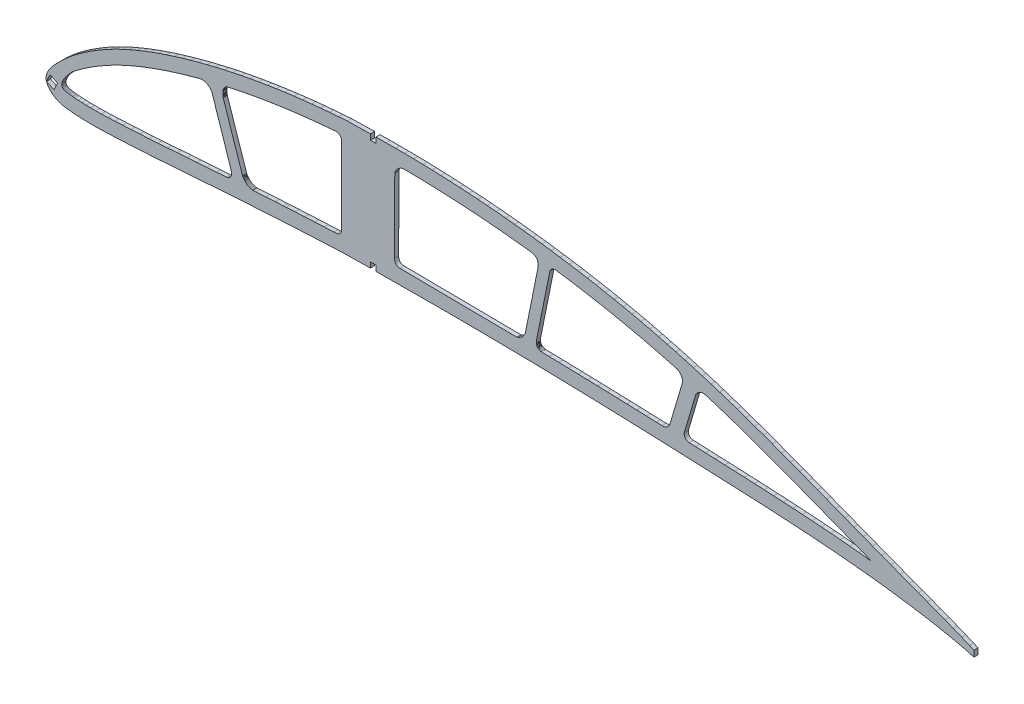
SolidWorks part; units mm, degrees
ref_plane "前视基准面" through (0, 0, 0) normal (0, 0, 1) x (1, 0, 0)
ref_plane "上视基准面" through (0, 0, 0) normal (0, 1, 0) x (1, 0, 0)
ref_plane "右视基准面" through (0, 0, 0) normal (1, 0, 0) x (0, 0, -1)
sketch "Model" plane through (0, 0, 0) normal (0, 0, 1) x (1, 0, 0)
  line L0 (1022.286, 336.2321) -> (1020.7448, 336.9192)
  line L1 (1020.7448, 336.9192) -> (1017.8583, 338.1132)
  line L2 (1017.8583, 338.1132) -> (1014.8751, 339.3165)
  line L3 (1014.8751, 339.3165) -> (1011.8129, 340.5212)
  line L4 (1011.8129, 340.5212) -> (1008.6699, 341.7323)
  line L5 (1008.6699, 341.7323) -> (1005.4593, 342.9542)
  line L6 (1005.4593, 342.9542) -> (1002.1944, 344.1881)
  line L7 (1002.1944, 344.1881) -> (998.8984, 345.4387)
  line L8 (998.8984, 345.4387) -> (995.5847, 346.6974)
  line L9 (995.5847, 346.6974) -> (992.2646, 347.9654)
  line L10 (992.2646, 347.9654) -> (988.9329, 349.242)
  line L11 (988.9329, 349.242) -> (985.6004, 350.5217)
  line L12 (985.6004, 350.5217) -> (982.2711, 351.8053)
  line L13 (982.2711, 351.8053) -> (978.9429, 353.0897)
  line L14 (978.9429, 353.0897) -> (975.6264, 354.3705)
  line L15 (975.6264, 354.3705) -> (972.3288, 355.6473)
  line L16 (972.3288, 355.6473) -> (969.0448, 356.9153)
  line L17 (969.0448, 356.9153) -> (965.7657, 358.1831)
  line L18 (965.7657, 358.1831) -> (962.4835, 359.449)
  line L19 (962.4835, 359.449) -> (959.198, 360.709)
  line L20 (959.198, 360.709) -> (955.9258, 361.9574)
  line L21 (955.9258, 361.9574) -> (952.6697, 363.1878)
  line L22 (952.6697, 363.1878) -> (949.4325, 364.3981)
  line L23 (949.4325, 364.3981) -> (946.2208, 365.58)
  line L24 (946.2208, 365.58) -> (943.0196, 366.7353)
  line L25 (943.0196, 366.7353) -> (939.8361, 367.8645)
  line L26 (939.8361, 367.8645) -> (936.6717, 368.9607)
  line L27 (936.6717, 368.9607) -> (933.5134, 370.0224)
  line L28 (933.5134, 370.0224) -> (930.3587, 371.058)
  line L29 (930.3587, 371.058) -> (927.213, 372.0559)
  line L30 (927.213, 372.0559) -> (924.0586, 373.0254)
  line L31 (924.0586, 373.0254) -> (920.9037, 373.9657)
  line L32 (920.9037, 373.9657) -> (917.7469, 374.8732)
  line L33 (917.7469, 374.8732) -> (914.5824, 375.75)
  line L34 (914.5824, 375.75) -> (911.4094, 376.5983)
  line L35 (911.4094, 376.5983) -> (908.2347, 377.4166)
  line L36 (908.2347, 377.4166) -> (905.0532, 378.2022)
  line L37 (905.0532, 378.2022) -> (901.8641, 378.9602)
  line L38 (901.8641, 378.9602) -> (898.6692, 379.6844)
  line L39 (898.6692, 379.6844) -> (895.4657, 380.3811)
  line L40 (895.4657, 380.3811) -> (892.2534, 381.0453)
  line L41 (892.2534, 381.0453) -> (889.0296, 381.681)
  line L42 (889.0296, 381.681) -> (885.7941, 382.2873)
  line L43 (885.7941, 382.2873) -> (882.5492, 382.8681)
  line L44 (882.5492, 382.8681) -> (879.2985, 383.4172)
  line L45 (879.2985, 383.4172) -> (876.0333, 383.9391)
  line L46 (876.0333, 383.9391) -> (872.7536, 384.4336)
  line L47 (872.7536, 384.4336) -> (869.4666, 384.9046)
  line L48 (869.4666, 384.9046) -> (866.171, 385.348)
  line L49 (866.171, 385.348) -> (862.8701, 385.7676)
  line L50 (862.8701, 385.7676) -> (859.5637, 386.1586)
  line L51 (859.5637, 386.1586) -> (856.2539, 386.5256)
  line L52 (856.2539, 386.5256) -> (852.9405, 386.8648)
  line L53 (852.9405, 386.8648) -> (849.6238, 387.1792)
  line L54 (849.6238, 387.1792) -> (846.3105, 387.4653)
  line L55 (846.3105, 387.4653) -> (842.9917, 387.7237)
  line L56 (842.9917, 387.7237) -> (839.6727, 387.9591)
  line L57 (839.6727, 387.9591) -> (836.3569, 388.1642)
  line L58 (836.3569, 388.1642) -> (833.0367, 388.3426)
  line L59 (833.0367, 388.3426) -> (829.7211, 388.4956)
  line L60 (829.7211, 388.4956) -> (826.4078, 388.6175)
  line L61 (826.4078, 388.6175) -> (823.0911, 388.7145)
  line L62 (823.0911, 388.7145) -> (819.7848, 388.7829)
  line L63 (819.7848, 388.7829) -> (816.4758, 388.8195)
  line L64 (816.4758, 388.8195) -> (813.1705, 388.8317)
  line L65 (813.1705, 388.8317) -> (809.8724, 388.8126)
  line L66 (804.1742, 388.8126) -> (795.9081, 388.6493)
  line L67 (795.9081, 388.6493) -> (792.643, 388.4151)
  line L68 (792.643, 388.4151) -> (789.3827, 388.1487)
  line L69 (789.3827, 388.1487) -> (786.1315, 387.855)
  line L70 (786.1315, 387.855) -> (782.8951, 387.5287)
  line L71 (782.8951, 387.5287) -> (779.6686, 387.1701)
  line L72 (779.6686, 387.1701) -> (776.4591, 386.7809)
  line L73 (776.4591, 386.7809) -> (773.2633, 386.3562)
  line L74 (773.2633, 386.3562) -> (770.0814, 385.8979)
  line L75 (770.0814, 385.8979) -> (766.9153, 385.4051)
  line L76 (766.9153, 385.4051) -> (763.7629, 384.8768)
  line L77 (763.7629, 384.8768) -> (760.6273, 384.3129)
  line L78 (760.6273, 384.3129) -> (757.5044, 383.7125)
  line L79 (757.5044, 383.7125) -> (754.4034, 383.0784)
  line L80 (754.4034, 383.0784) -> (751.318, 382.4036)
  line L81 (751.318, 382.4036) -> (748.2524, 381.6942)
  line L82 (748.2524, 381.6942) -> (745.2074, 380.947)
  line L83 (745.2074, 380.947) -> (742.1873, 380.1649)
  line L84 (742.1873, 380.1649) -> (739.1939, 379.3459)
  line L85 (739.1939, 379.3459) -> (736.2415, 378.4974)
  line L86 (736.2415, 378.4974) -> (733.3308, 377.6105)
  line L87 (733.3308, 377.6105) -> (730.465, 376.6919)
  line L88 (730.465, 376.6919) -> (727.6549, 375.7364)
  line L89 (727.6549, 375.7364) -> (724.8998, 374.749)
  line L90 (724.8998, 374.749) -> (722.2136, 373.7301)
  line L91 (722.2136, 373.7301) -> (719.5982, 372.6777)
  line L92 (719.5982, 372.6777) -> (717.0609, 371.5956)
  line L93 (717.0609, 371.5956) -> (714.6128, 370.4894)
  line L94 (714.6128, 370.4894) -> (712.2616, 369.3497)
  line L95 (712.2616, 369.3497) -> (710.0006, 368.1849)
  line L96 (710.0006, 368.1849) -> (707.8441, 367.0035)
  line L97 (707.8441, 367.0035) -> (705.7994, 365.8161)
  line L98 (705.7994, 365.8161) -> (703.878, 364.6344)
  line L99 (703.878, 364.6344) -> (702.0895, 363.4762)
  line L100 (702.0895, 363.4762) -> (700.4433, 362.3549)
  line L101 (700.4433, 362.3549) -> (698.944, 361.2826)
  line L102 (698.944, 361.2826) -> (697.5895, 360.2612)
  line L103 (697.5895, 360.2612) -> (696.3691, 359.2972)
  line L104 (696.3691, 359.2972) -> (695.2749, 358.3929)
  line L105 (695.2749, 358.3929) -> (694.2956, 357.5425)
  line L106 (694.2956, 357.5425) -> (693.4173, 356.7467)
  line L107 (693.4173, 356.7467) -> (692.627, 356.0058)
  line L108 (692.627, 356.0058) -> (691.9154, 355.3143)
  line L109 (691.9154, 355.3143) -> (691.2705, 354.6704)
  line L110 (691.2705, 354.6704) -> (690.6843, 354.0705)
  line L111 (690.6843, 354.0705) -> (690.1504, 353.5098)
  line L112 (690.1504, 353.5098) -> (689.6686, 352.9802)
  line L113 (689.6686, 352.9802) -> (689.2317, 352.4752)
  line L114 (689.2317, 352.4752) -> (688.8386, 351.9916)
  line L115 (688.8386, 351.9916) -> (688.4861, 351.5246)
  line L116 (688.4861, 351.5246) -> (688.1691, 351.0734)
  line L117 (688.1691, 351.0734) -> (687.8867, 350.635)
  line L118 (687.8867, 350.635) -> (687.6415, 350.2063)
  line L119 (687.6415, 350.2063) -> (687.4317, 349.7854)
  line L120 (687.4317, 349.7854) -> (687.2532, 349.3733)
  line L121 (687.2532, 349.3733) -> (687.113, 348.967)
  line L122 (687.113, 348.967) -> (687.0099, 348.5663)
  line L123 (687.0099, 348.5663) -> (686.9402, 348.1745)
  line L124 (686.9402, 348.1745) -> (686.8834, 347.7913)
  line L125 (696.7697, 346.626) -> (697.3134, 346.5805)
  line L126 (697.3134, 346.5805) -> (698.5153, 346.4985)
  line L127 (698.5153, 346.4985) -> (699.8508, 346.4339)
  line L128 (699.8508, 346.4339) -> (701.339, 346.3829)
  line L129 (701.339, 346.3829) -> (702.999, 346.3559)
  line L130 (702.999, 346.3559) -> (704.8532, 346.3582)
  line L131 (704.8532, 346.3582) -> (706.9208, 346.3951)
  line L132 (706.9208, 346.3951) -> (709.2289, 346.4736)
  line L133 (709.2289, 346.4736) -> (711.7863, 346.5844)
  line L134 (711.7863, 346.5844) -> (714.59, 346.7246)
  line L135 (714.59, 346.7246) -> (717.5963, 346.8828)
  line L136 (717.5963, 346.8828) -> (720.7605, 347.0625)
  line L137 (720.7605, 347.0625) -> (724.0344, 347.2614)
  line L138 (724.0344, 347.2614) -> (727.4003, 347.485)
  line L139 (727.4003, 347.485) -> (730.8387, 347.7222)
  line L140 (730.8387, 347.7222) -> (734.3316, 347.9734)
  line L141 (734.3316, 347.9734) -> (737.8666, 348.2282)
  line L142 (737.8666, 348.2282) -> (741.4197, 348.4854)
  line L143 (741.4197, 348.4854) -> (744.9788, 348.7403)
  line L144 (744.9788, 348.7403) -> (748.5347, 348.9904)
  line L145 (748.5347, 348.9904) -> (752.0884, 349.2345)
  line L146 (752.0884, 349.2345) -> (752.6695, 349.2734)
  line L147 (761.6695, 349.8624) -> (762.7382, 349.9302)
  line L148 (762.7382, 349.9302) -> (766.2809, 350.1487)
  line L149 (766.2809, 350.1487) -> (769.8144, 350.3596)
  line L150 (769.8144, 350.3596) -> (772.7598, 350.5276)
  line L151 (773.8054, 350.5865) -> (776.8806, 350.7572)
  line L152 (776.8806, 350.7572) -> (780.4062, 350.9423)
  line L153 (780.4062, 350.9423) -> (783.9347, 351.1232)
  line L154 (783.9347, 351.1232) -> (787.4499, 351.2957)
  line L155 (787.4499, 351.2957) -> (790.9736, 351.4558)
  line L156 (790.9736, 351.4558) -> (791.8586, 351.4954)
  line L157 (793.7692, 353.4934) -> (793.7692, 381.3561)
  line L158 (791.5892, 383.348) -> (786.1315, 382.855)
  line L159 (786.1315, 382.855) -> (782.8951, 382.5287)
  line L160 (782.8951, 382.5287) -> (779.6686, 382.1701)
  line L161 (779.6686, 382.1701) -> (776.4591, 381.7809)
  line L162 (776.4591, 381.7809) -> (773.2633, 381.3562)
  line L163 (773.2633, 381.3562) -> (770.0814, 380.8979)
  line L164 (770.0814, 380.8979) -> (769.1604, 380.7546)
  line L165 (769.1604, 380.7546) -> (766.9153, 380.4051)
  line L166 (766.9153, 380.4051) -> (763.7629, 379.8768)
  line L167 (763.7629, 379.8768) -> (760.6273, 379.3129)
  line L168 (760.6273, 379.3129) -> (757.5044, 378.7125)
  line L169 (757.5044, 378.7125) -> (754.4034, 378.0784)
  line L170 (754.4034, 378.0784) -> (752.0635, 377.5667)
  line L171 (743.0715, 375.3939) -> (742.1873, 375.1649)
  line L172 (742.1873, 375.1649) -> (739.1939, 374.3459)
  line L173 (739.1939, 374.3459) -> (736.2415, 373.4974)
  line L174 (736.2415, 373.4974) -> (733.3308, 372.6105)
  line L175 (733.3308, 372.6105) -> (730.465, 371.6919)
  line L176 (730.465, 371.6919) -> (727.6549, 370.7364)
  line L177 (727.6549, 370.7364) -> (724.8998, 369.749)
  line L178 (724.8998, 369.749) -> (722.2136, 368.7301)
  line L179 (722.2136, 368.7301) -> (719.5982, 367.6777)
  line L180 (719.5982, 367.6777) -> (717.0609, 366.5956)
  line L181 (717.0609, 366.5956) -> (714.6128, 365.4894)
  line L182 (714.6128, 365.4894) -> (712.2616, 364.3497)
  line L183 (712.2616, 364.3497) -> (710.0006, 363.1849)
  line L184 (710.0006, 363.1849) -> (707.8441, 362.0035)
  line L185 (707.8441, 362.0035) -> (705.7994, 360.8161)
  line L186 (705.7994, 360.8161) -> (703.878, 359.6344)
  line L187 (703.878, 359.6344) -> (702.0895, 358.4762)
  line L188 (702.0895, 358.4762) -> (700.4433, 357.3549)
  line L189 (700.4433, 357.3549) -> (698.944, 356.2826)
  line L190 (698.944, 356.2826) -> (697.5895, 355.2612)
  line L191 (697.5895, 355.2612) -> (696.3691, 354.2972)
  line L192 (696.3691, 354.2972) -> (695.2895, 353.0814)
  line L193 (865.925, 351.4512) -> (868.6951, 351.3931)
  line L194 (868.6951, 351.3931) -> (872.2281, 351.3142)
  line L195 (872.2281, 351.3142) -> (875.7398, 351.2294)
  line L196 (875.7398, 351.2294) -> (879.2421, 351.1392)
  line L197 (879.2421, 351.1392) -> (882.7382, 351.0443)
  line L198 (882.7382, 351.0443) -> (886.2429, 350.9419)
  line L199 (886.2429, 350.9419) -> (889.7575, 350.8379)
  line L200 (919.3445, 349.7485) -> (921.7276, 349.6493)
  line L201 (921.7276, 349.6493) -> (925.2507, 349.4988)
  line L202 (925.2507, 349.4988) -> (928.7739, 349.3503)
  line L203 (928.7739, 349.3503) -> (932.3076, 349.1942)
  line L204 (932.3076, 349.1942) -> (935.8494, 349.0387)
  line L205 (935.8494, 349.0387) -> (939.387, 348.8784)
  line L206 (939.387, 348.8784) -> (942.9181, 348.7104)
  line L207 (942.9181, 348.7104) -> (946.4389, 348.537)
  line L208 (946.4389, 348.537) -> (949.9382, 348.3558)
  line L209 (949.9382, 348.3558) -> (953.4248, 348.1612)
  line L210 (953.4248, 348.1612) -> (956.8948, 347.9566)
  line L211 (956.8948, 347.9566) -> (960.3419, 347.7372)
  line L212 (960.3419, 347.7372) -> (963.7792, 347.5013)
  line L213 (963.7792, 347.5013) -> (967.1925, 347.2507)
  line L214 (967.1925, 347.2507) -> (970.5938, 346.9807)
  line L215 (970.5938, 346.9807) -> (973.973, 346.692)
  line L216 (973.973, 346.692) -> (977.344, 346.3806)
  line L217 (977.344, 346.3806) -> (980.694, 346.0524)
  line L218 (980.694, 346.0524) -> (984.0237, 345.7003)
  line L219 (984.0237, 345.7003) -> (985.4644, 345.5361)
  line L220 (985.4644, 345.5361) -> (982.1698, 346.8063)
  line L221 (982.1698, 346.8063) -> (978.8416, 348.0907)
  line L222 (978.8416, 348.0907) -> (975.5252, 349.3716)
  line L223 (975.5252, 349.3716) -> (972.2275, 350.6483)
  line L224 (972.2275, 350.6483) -> (968.9435, 351.9163)
  line L225 (968.9435, 351.9163) -> (965.6644, 353.1841)
  line L226 (965.6644, 353.1841) -> (962.3822, 354.45)
  line L227 (962.3822, 354.45) -> (959.0967, 355.7101)
  line L228 (959.0967, 355.7101) -> (955.8245, 356.9584)
  line L229 (955.8245, 356.9584) -> (952.5684, 358.1888)
  line L230 (952.5684, 358.1888) -> (949.3312, 359.3991)
  line L231 (949.3312, 359.3991) -> (946.1195, 360.581)
  line L232 (946.1195, 360.581) -> (942.9183, 361.7363)
  line L233 (942.9183, 361.7363) -> (939.7348, 362.8656)
  line L234 (939.7348, 362.8656) -> (936.5704, 363.9617)
  line L235 (936.5704, 363.9617) -> (933.4121, 365.0235)
  line L236 (933.4121, 365.0235) -> (930.2574, 366.059)
  line L237 (930.2574, 366.059) -> (927.1117, 367.057)
  line L238 (927.1117, 367.057) -> (925.3841, 367.5879)
  line L239 (893.0335, 350.7311) -> (893.2976, 350.7225)
  line L240 (893.2976, 350.7225) -> (896.8525, 350.6053)
  line L241 (896.8525, 350.6053) -> (900.4081, 350.4811)
  line L242 (900.4081, 350.4811) -> (903.9713, 350.3514)
  line L243 (903.9713, 350.3514) -> (907.5345, 350.2197)
  line L244 (907.5345, 350.2197) -> (909.5076, 350.143)
  line L245 (914.7457, 370.6777) -> (914.4811, 370.751)
  line L246 (914.4811, 370.751) -> (911.3081, 371.5993)
  line L247 (911.3081, 371.5993) -> (908.1334, 372.4176)
  line L248 (908.1334, 372.4176) -> (904.9519, 373.2032)
  line L249 (904.9519, 373.2032) -> (901.7628, 373.9612)
  line L250 (901.7628, 373.9612) -> (898.5679, 374.6855)
  line L251 (898.5679, 374.6855) -> (895.3644, 375.3822)
  line L252 (895.3644, 375.3822) -> (892.1521, 376.0463)
  line L253 (892.1521, 376.0463) -> (888.9283, 376.682)
  line L254 (888.9283, 376.682) -> (885.6928, 377.2884)
  line L255 (885.6928, 377.2884) -> (882.4479, 377.8692)
  line L256 (882.4479, 377.8692) -> (879.1972, 378.4182)
  line L257 (879.1972, 378.4182) -> (875.932, 378.9401)
  line L258 (875.932, 378.9401) -> (872.6523, 379.4347)
  line L259 (872.6523, 379.4347) -> (870.8578, 379.6918)
  line L260 (862.7686, 380.7686) -> (859.4624, 381.1596)
  line L261 (859.4624, 381.1596) -> (856.1526, 381.5266)
  line L262 (856.1526, 381.5266) -> (852.8392, 381.8659)
  line L263 (852.8392, 381.8659) -> (849.5225, 382.1802)
  line L264 (849.5225, 382.1802) -> (846.2093, 382.4663)
  line L265 (846.2093, 382.4663) -> (842.8904, 382.7247)
  line L266 (842.8904, 382.7247) -> (839.5714, 382.9601)
  line L267 (839.5714, 382.9601) -> (836.2556, 383.1652)
  line L268 (836.2556, 383.1652) -> (832.9354, 383.3436)
  line L269 (832.9354, 383.3436) -> (829.6198, 383.4967)
  line L270 (829.6198, 383.4967) -> (826.3065, 383.6185)
  line L271 (826.3065, 383.6185) -> (822.9898, 383.7156)
  line L272 (822.9898, 383.7156) -> (819.6835, 383.784)
  line L273 (819.6835, 383.784) -> (816.1179, 383.8233)
  line L274 (812.9548, 380.9553) -> (812.8692, 354.1207)
  line L275 (814.8472, 352.0325) -> (833.6663, 351.8437)
  line L276 (835.9776, 351.8205) -> (857.1074, 351.6086)
  line L277 (686.8834, 347.7913) -> (686.891, 347.4068)
  line L278 (686.891, 347.4068) -> (686.9454, 347.0167)
  line L279 (686.9454, 347.0167) -> (687.0478, 346.6258)
  line L280 (687.0478, 346.6258) -> (687.1944, 346.2385)
  line L281 (687.1944, 346.2385) -> (687.3842, 345.8566)
  line L282 (687.3842, 345.8566) -> (687.6163, 345.4823)
  line L283 (687.6163, 345.4823) -> (687.8867, 345.1166)
  line L284 (687.8867, 345.1166) -> (688.1933, 344.7577)
  line L285 (688.1933, 344.7577) -> (688.5374, 344.4095)
  line L286 (688.5374, 344.4095) -> (688.9179, 344.072)
  line L287 (688.9179, 344.072) -> (689.3325, 343.7404)
  line L288 (689.3325, 343.7404) -> (689.7869, 343.4263)
  line L289 (689.7869, 343.4263) -> (690.2837, 343.1268)
  line L290 (690.2837, 343.1268) -> (690.8212, 342.8449)
  line L291 (690.8212, 342.8449) -> (691.4066, 342.5873)
  line L292 (691.4066, 342.5873) -> (692.0442, 342.3649)
  line L293 (692.0442, 342.3649) -> (692.7378, 342.1696)
  line L294 (692.7378, 342.1696) -> (693.4906, 342.0082)
  line L295 (693.4906, 342.0082) -> (694.3126, 341.8774)
  line L296 (694.3126, 341.8774) -> (695.2112, 341.767)
  line L297 (695.2112, 341.767) -> (696.1975, 341.6715)
  line L298 (696.1975, 341.6715) -> (697.285, 341.5805)
  line L299 (697.285, 341.5805) -> (698.4869, 341.4985)
  line L300 (698.4869, 341.4985) -> (699.8224, 341.4339)
  line L301 (699.8224, 341.4339) -> (701.3106, 341.3829)
  line L302 (701.3106, 341.3829) -> (702.9706, 341.3559)
  line L303 (702.9706, 341.3559) -> (704.8248, 341.3582)
  line L304 (704.8248, 341.3582) -> (706.8924, 341.3951)
  line L305 (706.8924, 341.3951) -> (709.2005, 341.4736)
  line L306 (709.2005, 341.4736) -> (711.758, 341.5844)
  line L307 (711.758, 341.5844) -> (714.5616, 341.7246)
  line L308 (714.5616, 341.7246) -> (717.5679, 341.8828)
  line L309 (717.5679, 341.8828) -> (720.7321, 342.0625)
  line L310 (720.7321, 342.0625) -> (724.006, 342.2614)
  line L311 (724.006, 342.2614) -> (727.3719, 342.485)
  line L312 (727.3719, 342.485) -> (730.8103, 342.7222)
  line L313 (730.8103, 342.7222) -> (734.3032, 342.9734)
  line L314 (734.3032, 342.9734) -> (737.8382, 343.2282)
  line L315 (737.8382, 343.2282) -> (741.3914, 343.4854)
  line L316 (741.3914, 343.4854) -> (744.9504, 343.7403)
  line L317 (744.9504, 343.7403) -> (748.5063, 343.9904)
  line L318 (748.5063, 343.9904) -> (752.06, 344.2345)
  line L319 (752.06, 344.2345) -> (755.6125, 344.4727)
  line L320 (755.6125, 344.4727) -> (759.1627, 344.7049)
  line L321 (759.1627, 344.7049) -> (762.7098, 344.9302)
  line L322 (762.7098, 344.9302) -> (766.2525, 345.1487)
  line L323 (766.2525, 345.1487) -> (769.7861, 345.3596)
  line L324 (769.7861, 345.3596) -> (773.3223, 345.5613)
  line L325 (773.3223, 345.5613) -> (776.8522, 345.7572)
  line L326 (776.8522, 345.7572) -> (780.3778, 345.9423)
  line L327 (780.3778, 345.9423) -> (783.9063, 346.1232)
  line L328 (783.9063, 346.1232) -> (787.4215, 346.2957)
  line L329 (787.4215, 346.2957) -> (790.9452, 346.4558)
  line L330 (790.9452, 346.4558) -> (794.4729, 346.6138)
  line L331 (794.4729, 346.6138) -> (800.6969, 346.6976)
  line L332 (688.3447, 349.3764) -> (691.0509, 348.0815)
  line L333 (691.0509, 348.0815) -> (689.756, 345.3753)
  line L334 (689.756, 345.3753) -> (687.0498, 346.6702)
  line L335 (688.3447, 349.3764) -> (687.0498, 346.6702)
  line L336 (800.6969, 346.6976) -> (803.1743, 346.7458)
  line L337 (812.0628, 346.7458) -> (806.1742, 346.7458)
  line L338 (812.0628, 346.7458) -> (815.578, 346.78)
  line L339 (815.578, 346.78) -> (819.0899, 346.8074)
  line L340 (819.0899, 346.8074) -> (822.5903, 346.8264)
  line L341 (822.5903, 346.8264) -> (826.0981, 346.835)
  line L342 (826.0981, 346.835) -> (829.6077, 346.8395)
  line L343 (829.6077, 346.8395) -> (833.1297, 346.8343)
  line L344 (833.1297, 346.8343) -> (836.6525, 346.824)
  line L345 (836.6525, 346.824) -> (840.1868, 346.8031)
  line L346 (840.1868, 346.8031) -> (843.7286, 346.7758)
  line L347 (843.7286, 346.7758) -> (847.2741, 346.7412)
  line L348 (847.2741, 346.7412) -> (850.8232, 346.6995)
  line L349 (850.8232, 346.6995) -> (854.3739, 346.6506)
  line L350 (854.3739, 346.6506) -> (857.9303, 346.5954)
  line L351 (857.9303, 346.5954) -> (861.4814, 346.5355)
  line L352 (861.4814, 346.5355) -> (865.0271, 346.4689)
  line L353 (865.0271, 346.4689) -> (868.5654, 346.3947)
  line L354 (868.5654, 346.3947) -> (872.0984, 346.3158)
  line L355 (872.0984, 346.3158) -> (875.6101, 346.231)
  line L356 (875.6101, 346.231) -> (879.1125, 346.1408)
  line L357 (879.1125, 346.1408) -> (882.6085, 346.0459)
  line L358 (882.6085, 346.0459) -> (886.1132, 345.9435)
  line L359 (886.1132, 345.9435) -> (889.6278, 345.8395)
  line L360 (889.6278, 345.8395) -> (893.1679, 345.7241)
  line L361 (893.1679, 345.7241) -> (896.7228, 345.6069)
  line L362 (896.7228, 345.6069) -> (900.2784, 345.4827)
  line L363 (900.2784, 345.4827) -> (903.8416, 345.353)
  line L364 (903.8416, 345.353) -> (907.4048, 345.2213)
  line L365 (907.4048, 345.2213) -> (910.9596, 345.0831)
  line L366 (910.9596, 345.0831) -> (914.5152, 344.9409)
  line L367 (914.5152, 344.9409) -> (918.0647, 344.7979)
  line L368 (918.0647, 344.7979) -> (921.5979, 344.6509)
  line L369 (921.5979, 344.6509) -> (925.121, 344.5004)
  line L370 (925.121, 344.5004) -> (928.6442, 344.3519)
  line L371 (928.6442, 344.3519) -> (932.1779, 344.1958)
  line L372 (932.1779, 344.1958) -> (935.7198, 344.0403)
  line L373 (935.7198, 344.0403) -> (939.2573, 343.88)
  line L374 (939.2573, 343.88) -> (942.7884, 343.712)
  line L375 (942.7884, 343.712) -> (946.3092, 343.5386)
  line L376 (946.3092, 343.5386) -> (949.8085, 343.3574)
  line L377 (949.8085, 343.3574) -> (953.2951, 343.1628)
  line L378 (953.2951, 343.1628) -> (956.7651, 342.9582)
  line L379 (956.7651, 342.9582) -> (960.2123, 342.7388)
  line L380 (960.2123, 342.7388) -> (963.6495, 342.5029)
  line L381 (963.6495, 342.5029) -> (967.0629, 342.2523)
  line L382 (967.0629, 342.2523) -> (970.4641, 341.9823)
  line L383 (970.4641, 341.9823) -> (973.8434, 341.6936)
  line L384 (973.8434, 341.6936) -> (977.2143, 341.3822)
  line L385 (977.2143, 341.3822) -> (980.5643, 341.054)
  line L386 (980.5643, 341.054) -> (983.894, 340.7019)
  line L387 (983.894, 340.7019) -> (987.2032, 340.3248)
  line L388 (987.2032, 340.3248) -> (990.5, 339.9224)
  line L389 (990.5, 339.9224) -> (993.7678, 339.5006)
  line L390 (993.7678, 339.5006) -> (997.0039, 339.0515)
  line L391 (997.0039, 339.0515) -> (1000.2087, 338.5791)
  line L392 (1000.2087, 338.5791) -> (1003.3622, 338.0834)
  line L393 (1003.3622, 338.0834) -> (1006.4602, 337.5618)
  line L394 (1006.4602, 337.5618) -> (1009.4864, 337.0121)
  line L395 (1009.4864, 337.0121) -> (1012.4496, 336.4258)
  line L396 (1012.4496, 336.4258) -> (1015.3379, 335.8076)
  line L397 (1015.3379, 335.8076) -> (1018.1529, 335.1484)
  line L398 (1018.1529, 335.1484) -> (1020.8918, 334.4543)
  line L399 (1020.8918, 334.4543) -> (1022.286, 334.0188)
  line L400 (804.1742, 386.8126) -> (806.1742, 386.8126)
  line L401 (804.1742, 348.7458) -> (806.1742, 348.7458)
  line L402 (806.1742, 386.8126) -> (806.1742, 388.8126)
  line L403 (804.1742, 386.8126) -> (804.1742, 388.8126)
  line L404 (806.1742, 348.7458) -> (806.1742, 346.7458)
  line L405 (804.1742, 348.7458) -> (804.1742, 346.7653)
  line L406 (806.1742, 388.8126) -> (809.8724, 388.8126)
  line L407 (1022.286, 336.2321) -> (1022.286, 334.0188)
  line L408 (803.1743, 346.7458) -> (804.1742, 346.7653)
  line L409 (864.815, 377.6104) -> (860.0887, 354.1475)
  line L410 (864.1581, 354.08) -> (869.0351, 378.3064)
  line L411 (916.8221, 366.9378) -> (912.5016, 352.2919)
  line L412 (921.6358, 365.6035) -> (917.5942, 351.9038)
  line L413 (889.7575, 350.8379) -> (893.0335, 350.7311)
  line L414 (772.7598, 350.5276) -> (773.8054, 350.5865)
  line L415 (746.7395, 373.5254) -> (753.7495, 352.4684)
  line L416 (750.9495, 373.4154) -> (757.9295, 352.5404)
  line L417 (833.6663, 351.8437) -> (835.9776, 351.8205)
  line L418 (695.2895, 353.0814) -> (695.2595, 353.0434)
  line L419 (695.2595, 353.0434) -> (695.2195, 353.0044)
  line L420 (695.2195, 353.0044) -> (695.1895, 352.9654)
  line L421 (695.1895, 352.9654) -> (695.1495, 352.9264)
  line L422 (695.1495, 352.9264) -> (695.1195, 352.8874)
  line L423 (695.1195, 352.8874) -> (695.0795, 352.8494)
  line L424 (695.0795, 352.8494) -> (695.0495, 352.8104)
  line L425 (695.0495, 352.8104) -> (695.0095, 352.7714)
  line L426 (695.0095, 352.7714) -> (694.9795, 352.7324)
  line L427 (694.9795, 352.7324) -> (694.9395, 352.6934)
  line L428 (694.9395, 352.6934) -> (694.9095, 352.6544)
  line L429 (694.9095, 352.6544) -> (694.8795, 352.6154)
  line L430 (694.8795, 352.6154) -> (694.8395, 352.5764)
  line L431 (694.8395, 352.5764) -> (694.8095, 352.5374)
  line L432 (694.8095, 352.5374) -> (694.7695, 352.4974)
  line L433 (694.7695, 352.4974) -> (694.7395, 352.4584)
  line L434 (694.7395, 352.4584) -> (694.6995, 352.4194)
  line L435 (694.6995, 352.4194) -> (694.6695, 352.3794)
  line L436 (694.6695, 352.3794) -> (694.6295, 352.3404)
  line L437 (694.6295, 352.3404) -> (694.5995, 352.3004)
  line L438 (694.5995, 352.3004) -> (694.5695, 352.2614)
  line L439 (694.5695, 352.2614) -> (694.5295, 352.2214)
  line L440 (694.5295, 352.2214) -> (694.4995, 352.1814)
  line L441 (694.4995, 352.1814) -> (694.4695, 352.1414)
  line L442 (694.4695, 352.1414) -> (694.4295, 352.1014)
  line L443 (694.4295, 352.1014) -> (694.3995, 352.0614)
  line L444 (694.3995, 352.0614) -> (694.3595, 352.0214)
  line L445 (694.3595, 352.0214) -> (694.3295, 351.9814)
  line L446 (694.3295, 351.9814) -> (694.2995, 351.9404)
  line L447 (694.2995, 351.9404) -> (694.2695, 351.9004)
  line L448 (694.2695, 351.9004) -> (694.2295, 351.8594)
  line L449 (694.2295, 351.8594) -> (694.1995, 351.8184)
  line L450 (694.1995, 351.8184) -> (694.1695, 351.7774)
  line L451 (694.1695, 351.7774) -> (694.1295, 351.7364)
  line L452 (694.1295, 351.7364) -> (694.0995, 351.6954)
  line L453 (694.0995, 351.6954) -> (694.0695, 351.6534)
  line L454 (694.0695, 351.6534) -> (694.0395, 351.6124)
  line L455 (694.0395, 351.6124) -> (694.0095, 351.5704)
  line L456 (694.0095, 351.5704) -> (693.9695, 351.5284)
  line L457 (693.9695, 351.5284) -> (693.9395, 351.4864)
  line L458 (693.9395, 351.4864) -> (693.9095, 351.4444)
  line L459 (693.9095, 351.4444) -> (693.8795, 351.4024)
  line L460 (693.8795, 351.4024) -> (693.8495, 351.3594)
  line L461 (693.8495, 351.3594) -> (693.8195, 351.3174)
  line L462 (693.8195, 351.3174) -> (693.7895, 351.2744)
  line L463 (693.7895, 351.2744) -> (693.7595, 351.2314)
  line L464 (693.7595, 351.2314) -> (693.7295, 351.1874)
  line L465 (693.7295, 351.1874) -> (693.6995, 351.1444)
  line L466 (693.6995, 351.1444) -> (693.6695, 351.1004)
  line L467 (693.6695, 351.1004) -> (693.6395, 351.0564)
  line L468 (693.6395, 351.0564) -> (693.6095, 351.0124)
  line L469 (693.6095, 351.0124) -> (693.5795, 350.9684)
  line L470 (693.5795, 350.9684) -> (693.5495, 350.9244)
  line L471 (693.5495, 350.9244) -> (693.5195, 350.8794)
  line L472 (693.5195, 350.8794) -> (693.4895, 350.8344)
  line L473 (693.4895, 350.8344) -> (693.4695, 350.7894)
  line L474 (693.4695, 350.7894) -> (693.4395, 350.7434)
  line L475 (693.4395, 350.7434) -> (693.4095, 350.6984)
  line L476 (693.4095, 350.6984) -> (693.3795, 350.6524)
  line L477 (693.3795, 350.6524) -> (693.3595, 350.6064)
  line L478 (693.3595, 350.6064) -> (693.3295, 350.5594)
  line L479 (693.3295, 350.5594) -> (693.2995, 350.5134)
  line L480 (693.2995, 350.5134) -> (693.2795, 350.4664)
  line L481 (693.2795, 350.4664) -> (693.2495, 350.4194)
  line L482 (693.2495, 350.4194) -> (693.2195, 350.3714)
  line L483 (693.2195, 350.3714) -> (693.1995, 350.3244)
  line L484 (693.1995, 350.3244) -> (693.1695, 350.2764)
  line L485 (693.1695, 350.2764) -> (693.1495, 350.2284)
  line L486 (693.1495, 350.2284) -> (693.1195, 350.1794)
  line L487 (693.1195, 350.1794) -> (693.0995, 350.1304)
  line L488 (693.0995, 350.1304) -> (693.0795, 350.0814)
  line L489 (693.0795, 350.0814) -> (693.0495, 350.0324)
  line L490 (693.0495, 350.0324) -> (693.0295, 349.9824)
  line L491 (693.0295, 349.9824) -> (692.9995, 349.9324)
  line L492 (692.9995, 349.9324) -> (692.9795, 349.8824)
  line L493 (692.9795, 349.8824) -> (692.9595, 349.8314)
  line L494 (692.9595, 349.8314) -> (692.9395, 349.7804)
  line L495 (692.9395, 349.7804) -> (692.9195, 349.7294)
  line L496 (692.9195, 349.7294) -> (692.8895, 349.6784)
  line L497 (692.8895, 349.6784) -> (692.8695, 349.6264)
  line L498 (692.8695, 349.6264) -> (692.8495, 349.5744)
  line L499 (692.8495, 349.5744) -> (692.8295, 349.5214)
  line L500 (692.8295, 349.5214) -> (692.8095, 349.4684)
  line L501 (692.8095, 349.4684) -> (692.7895, 349.4154)
  line L502 (692.7895, 349.4154) -> (692.7695, 349.3624)
  line L503 (692.7695, 349.3624) -> (692.7495, 349.3084)
  line L504 (692.7495, 349.3084) -> (692.7395, 349.2554)
  line L505 (692.7395, 349.2554) -> (692.7195, 349.2014)
  line L506 (692.7195, 349.2014) -> (692.6995, 349.1484)
  line L507 (692.6995, 349.1484) -> (692.6895, 349.0944)
  line L508 (692.6895, 349.0944) -> (692.6695, 349.0414)
  line L509 (692.6695, 349.0414) -> (692.6595, 348.9884)
  line L510 (692.6595, 348.9884) -> (692.6395, 348.9354)
  line L511 (692.6395, 348.9354) -> (692.6295, 348.8824)
  line L512 (692.6295, 348.8824) -> (692.6195, 348.8304)
  line L513 (692.6195, 348.8304) -> (692.6095, 348.7774)
  line L514 (692.6095, 348.7774) -> (692.5995, 348.7264)
  line L515 (692.5995, 348.7264) -> (692.5895, 348.6754)
  line L516 (692.5895, 348.6754) -> (692.5895, 348.6244)
  line L517 (692.5895, 348.6244) -> (692.5795, 348.5744)
  line L518 (692.5795, 348.5744) -> (692.5795, 348.5254)
  line L519 (692.5795, 348.5254) -> (692.5795, 348.4764)
  line L520 (692.5795, 348.4764) -> (692.5695, 348.4284)
  line L521 (692.5695, 348.4284) -> (692.5695, 348.3814)
  line L522 (692.5695, 348.3814) -> (692.5795, 348.3354)
  line L523 (692.5795, 348.3354) -> (692.5795, 348.2894)
  line L524 (692.5795, 348.2894) -> (692.5795, 348.2454)
  line L525 (692.5795, 348.2454) -> (692.5895, 348.2014)
  line L526 (692.5895, 348.2014) -> (692.5995, 348.1584)
  line L527 (692.5995, 348.1584) -> (692.6095, 348.1164)
  line L528 (692.6095, 348.1164) -> (692.6195, 348.0754)
  line L529 (692.6195, 348.0754) -> (692.6295, 348.0354)
  line L530 (692.6295, 348.0354) -> (692.6495, 347.9964)
  line L531 (692.6495, 347.9964) -> (692.6595, 347.9574)
  line L532 (692.6595, 347.9574) -> (692.6795, 347.9194)
  line L533 (692.6795, 347.9194) -> (692.6995, 347.8824)
  line L534 (692.6995, 347.8824) -> (692.7195, 347.8464)
  line L535 (692.7195, 347.8464) -> (692.7395, 347.8114)
  line L536 (692.7395, 347.8114) -> (692.7595, 347.7764)
  line L537 (692.7595, 347.7764) -> (692.7895, 347.7434)
  line L538 (692.7895, 347.7434) -> (692.8095, 347.7094)
  line L539 (692.8095, 347.7094) -> (692.8395, 347.6774)
  line L540 (692.8395, 347.6774) -> (692.8695, 347.6454)
  line L541 (692.8695, 347.6454) -> (692.8895, 347.6154)
  line L542 (692.8895, 347.6154) -> (692.9295, 347.5844)
  line L543 (692.9295, 347.5844) -> (692.9595, 347.5554)
  line L544 (692.9595, 347.5554) -> (692.9895, 347.5264)
  line L545 (692.9895, 347.5264) -> (693.0195, 347.4984)
  line L546 (693.0195, 347.4984) -> (693.0595, 347.4704)
  line L547 (693.0595, 347.4704) -> (693.0995, 347.4444)
  line L548 (693.0995, 347.4444) -> (693.1295, 347.4174)
  line L549 (693.1295, 347.4174) -> (693.1695, 347.3924)
  line L550 (693.1695, 347.3924) -> (693.2095, 347.3674)
  line L551 (693.2095, 347.3674) -> (693.2495, 347.3434)
  line L552 (693.2495, 347.3434) -> (693.2895, 347.3194)
  line L553 (693.2895, 347.3194) -> (693.3395, 347.2964)
  line L554 (693.3395, 347.2964) -> (693.3795, 347.2734)
  line L555 (693.3795, 347.2734) -> (693.4295, 347.2514)
  line L556 (693.4295, 347.2514) -> (693.4695, 347.2304)
  line L557 (693.4695, 347.2304) -> (693.5195, 347.2094)
  line L558 (693.5195, 347.2094) -> (693.5695, 347.1894)
  line L559 (693.5695, 347.1894) -> (693.6195, 347.1694)
  line L560 (693.6195, 347.1694) -> (693.6695, 347.1504)
  line L561 (693.6695, 347.1504) -> (693.7195, 347.1314)
  line L562 (693.7195, 347.1314) -> (693.7695, 347.1134)
  line L563 (693.7695, 347.1134) -> (693.8195, 347.0954)
  line L564 (693.8195, 347.0954) -> (693.8695, 347.0774)
  line L565 (693.8695, 347.0774) -> (693.9295, 347.0614)
  line L566 (693.9295, 347.0614) -> (693.9795, 347.0444)
  line L567 (693.9795, 347.0444) -> (694.0395, 347.0284)
  line L568 (694.0395, 347.0284) -> (694.0995, 347.0134)
  line L569 (694.0995, 347.0134) -> (694.1495, 346.9984)
  line L570 (694.1495, 346.9984) -> (694.2095, 346.9834)
  line L571 (694.2095, 346.9834) -> (694.2695, 346.9694)
  line L572 (694.2695, 346.9694) -> (694.3295, 346.9554)
  line L573 (694.3295, 346.9554) -> (694.3895, 346.9414)
  line L574 (694.3895, 346.9414) -> (694.4495, 346.9284)
  line L575 (694.4495, 346.9284) -> (694.5095, 346.9154)
  line L576 (694.5095, 346.9154) -> (694.5695, 346.9034)
  line L577 (694.5695, 346.9034) -> (694.6395, 346.8914)
  line L578 (694.6395, 346.8914) -> (694.6995, 346.8794)
  line L579 (694.6995, 346.8794) -> (694.7595, 346.8684)
  line L580 (694.7595, 346.8684) -> (694.8295, 346.8564)
  line L581 (694.8295, 346.8564) -> (694.8895, 346.8464)
  line L582 (694.8895, 346.8464) -> (694.9595, 346.8354)
  line L583 (694.9595, 346.8354) -> (695.0195, 346.8254)
  line L584 (695.0195, 346.8254) -> (695.0895, 346.8154)
  line L585 (695.0895, 346.8154) -> (695.1595, 346.8054)
  line L586 (695.1595, 346.8054) -> (695.2195, 346.7954)
  line L587 (695.2195, 346.7954) -> (695.2895, 346.7864)
  line L588 (695.2895, 346.7864) -> (695.3595, 346.7774)
  line L589 (695.3595, 346.7774) -> (695.4295, 346.7684)
  line L590 (695.4295, 346.7684) -> (695.4895, 346.7594)
  line L591 (695.4895, 346.7594) -> (695.5595, 346.7514)
  line L592 (695.5595, 346.7514) -> (695.6295, 346.7434)
  line L593 (695.6295, 346.7434) -> (695.6995, 346.7354)
  line L594 (695.6995, 346.7354) -> (695.7695, 346.7274)
  line L595 (695.7695, 346.7274) -> (695.8395, 346.7194)
  line L596 (695.8395, 346.7194) -> (695.9095, 346.7114)
  line L597 (695.9095, 346.7114) -> (695.9795, 346.7034)
  line L598 (695.9795, 346.7034) -> (696.0495, 346.6964)
  line L599 (696.0495, 346.6964) -> (696.1295, 346.6894)
  line L600 (696.1295, 346.6894) -> (696.1995, 346.6814)
  line L601 (696.1995, 346.6814) -> (696.2695, 346.6744)
  line L602 (696.2695, 346.6744) -> (696.3395, 346.6674)
  line L603 (696.3395, 346.6674) -> (696.4095, 346.6604)
  line L604 (696.4095, 346.6604) -> (696.4795, 346.6534)
  line L605 (696.4795, 346.6534) -> (696.5495, 346.6464)
  line L606 (696.5495, 346.6464) -> (696.6295, 346.6394)
  line L607 (696.6295, 346.6394) -> (696.6995, 346.6334)
  line L608 (696.6995, 346.6334) -> (696.7697, 346.626)
  line L609 (743.0715, 375.3939) -> (743.0995, 375.3904)
  line L610 (743.0995, 375.3904) -> (743.1295, 375.3874)
  line L611 (743.1295, 375.3874) -> (743.1495, 375.3844)
  line L612 (743.1495, 375.3844) -> (743.1795, 375.3814)
  line L613 (743.1795, 375.3814) -> (743.2095, 375.3784)
  line L614 (743.2095, 375.3784) -> (743.2395, 375.3754)
  line L615 (743.2395, 375.3754) -> (743.2595, 375.3724)
  line L616 (743.2595, 375.3724) -> (743.2895, 375.3694)
  line L617 (743.2895, 375.3694) -> (743.3195, 375.3664)
  line L618 (743.3195, 375.3664) -> (743.3495, 375.3624)
  line L619 (743.3495, 375.3624) -> (743.3695, 375.3594)
  line L620 (743.3695, 375.3594) -> (743.3995, 375.3564)
  line L621 (743.3995, 375.3564) -> (743.4295, 375.3534)
  line L622 (743.4295, 375.3534) -> (743.4595, 375.3494)
  line L623 (743.4595, 375.3494) -> (743.4795, 375.3464)
  line L624 (743.4795, 375.3464) -> (743.5095, 375.3424)
  line L625 (743.5095, 375.3424) -> (743.5395, 375.3394)
  line L626 (743.5395, 375.3394) -> (743.5595, 375.3364)
  line L627 (743.5595, 375.3364) -> (743.5895, 375.3324)
  line L628 (743.5895, 375.3324) -> (743.6195, 375.3284)
  line L629 (743.6195, 375.3284) -> (743.6495, 375.3254)
  line L630 (743.6495, 375.3254) -> (743.6695, 375.3214)
  line L631 (743.6695, 375.3214) -> (743.6995, 375.3174)
  line L632 (743.6995, 375.3174) -> (743.7295, 375.3134)
  line L633 (743.7295, 375.3134) -> (743.7495, 375.3094)
  line L634 (743.7495, 375.3094) -> (743.7795, 375.3054)
  line L635 (743.7795, 375.3054) -> (743.8095, 375.3014)
  line L636 (743.8095, 375.3014) -> (743.8395, 375.2974)
  line L637 (743.8395, 375.2974) -> (743.8595, 375.2934)
  line L638 (743.8595, 375.2934) -> (743.8895, 375.2894)
  line L639 (743.8895, 375.2894) -> (743.9195, 375.2844)
  line L640 (743.9195, 375.2844) -> (743.9395, 375.2804)
  line L641 (743.9395, 375.2804) -> (743.9695, 375.2754)
  line L642 (743.9695, 375.2754) -> (743.9995, 375.2714)
  line L643 (743.9995, 375.2714) -> (744.0195, 375.2664)
  line L644 (744.0195, 375.2664) -> (744.0495, 375.2614)
  line L645 (744.0495, 375.2614) -> (744.0795, 375.2564)
  line L646 (744.0795, 375.2564) -> (744.0995, 375.2514)
  line L647 (744.0995, 375.2514) -> (744.1295, 375.2464)
  line L648 (744.1295, 375.2464) -> (744.1595, 375.2414)
  line L649 (744.1595, 375.2414) -> (744.1795, 375.2364)
  line L650 (744.1795, 375.2364) -> (744.2095, 375.2304)
  line L651 (744.2095, 375.2304) -> (744.2295, 375.2254)
  line L652 (744.2295, 375.2254) -> (744.2595, 375.2194)
  line L653 (744.2595, 375.2194) -> (744.2895, 375.2134)
  line L654 (744.2895, 375.2134) -> (744.3095, 375.2074)
  line L655 (744.3095, 375.2074) -> (744.3395, 375.2014)
  line L656 (744.3395, 375.2014) -> (744.3595, 375.1954)
  line L657 (744.3595, 375.1954) -> (744.3895, 375.1894)
  line L658 (744.3895, 375.1894) -> (744.4195, 375.1824)
  line L659 (744.4195, 375.1824) -> (744.4395, 375.1764)
  line L660 (744.4395, 375.1764) -> (744.4695, 375.1694)
  line L661 (744.4695, 375.1694) -> (744.4895, 375.1624)
  line L662 (744.4895, 375.1624) -> (744.5195, 375.1554)
  line L663 (744.5195, 375.1554) -> (744.5395, 375.1484)
  line L664 (744.5395, 375.1484) -> (744.5695, 375.1404)
  line L665 (744.5695, 375.1404) -> (744.5895, 375.1334)
  line L666 (744.5895, 375.1334) -> (744.6195, 375.1254)
  line L667 (744.6195, 375.1254) -> (744.6395, 375.1174)
  line L668 (744.6395, 375.1174) -> (744.6695, 375.1094)
  line L669 (744.6695, 375.1094) -> (744.6895, 375.1014)
  line L670 (744.6895, 375.1014) -> (744.7195, 375.0934)
  line L671 (744.7195, 375.0934) -> (744.7395, 375.0844)
  line L672 (744.7395, 375.0844) -> (744.7695, 375.0764)
  line L673 (744.7695, 375.0764) -> (744.7895, 375.0674)
  line L674 (744.7895, 375.0674) -> (744.8195, 375.0584)
  line L675 (744.8195, 375.0584) -> (744.8395, 375.0494)
  line L676 (744.8395, 375.0494) -> (744.8695, 375.0394)
  line L677 (744.8695, 375.0394) -> (744.8895, 375.0304)
  line L678 (744.8895, 375.0304) -> (744.9095, 375.0204)
  line L679 (744.9095, 375.0204) -> (744.9395, 375.0104)
  line L680 (744.9395, 375.0104) -> (744.9595, 375.0004)
  line L681 (744.9595, 375.0004) -> (744.9895, 374.9904)
  line L682 (744.9895, 374.9904) -> (745.0095, 374.9794)
  line L683 (745.0095, 374.9794) -> (745.0295, 374.9684)
  line L684 (745.0295, 374.9684) -> (745.0595, 374.9574)
  line L685 (745.0595, 374.9574) -> (745.0795, 374.9464)
  line L686 (745.0795, 374.9464) -> (745.0995, 374.9354)
  line L687 (745.0995, 374.9354) -> (745.1295, 374.9234)
  line L688 (745.1295, 374.9234) -> (745.1495, 374.9114)
  line L689 (745.1495, 374.9114) -> (745.1695, 374.8994)
  line L690 (745.1695, 374.8994) -> (745.1995, 374.8874)
  line L691 (745.1995, 374.8874) -> (745.2195, 374.8754)
  line L692 (745.2195, 374.8754) -> (745.2395, 374.8624)
  line L693 (745.2395, 374.8624) -> (745.2595, 374.8494)
  line L694 (745.2595, 374.8494) -> (745.2895, 374.8364)
  line L695 (745.2895, 374.8364) -> (745.3095, 374.8234)
  line L696 (745.3095, 374.8234) -> (745.3295, 374.8094)
  line L697 (745.3295, 374.8094) -> (745.3495, 374.7964)
  line L698 (745.3495, 374.7964) -> (745.3695, 374.7824)
  line L699 (745.3695, 374.7824) -> (745.3995, 374.7684)
  line L700 (745.3995, 374.7684) -> (745.4195, 374.7544)
  line L701 (745.4195, 374.7544) -> (745.4395, 374.7394)
  line L702 (745.4395, 374.7394) -> (745.4595, 374.7254)
  line L703 (745.4595, 374.7254) -> (745.4795, 374.7104)
  line L704 (745.4795, 374.7104) -> (745.4995, 374.6954)
  line L705 (745.4995, 374.6954) -> (745.5295, 374.6804)
  line L706 (745.5295, 374.6804) -> (745.5495, 374.6654)
  line L707 (745.5495, 374.6654) -> (745.5695, 374.6494)
  line L708 (745.5695, 374.6494) -> (745.5895, 374.6344)
  line L709 (745.5895, 374.6344) -> (745.6095, 374.6184)
  line L710 (745.6095, 374.6184) -> (745.6295, 374.6024)
  line L711 (745.6295, 374.6024) -> (745.6495, 374.5864)
  line L712 (745.6495, 374.5864) -> (745.6695, 374.5704)
  line L713 (745.6695, 374.5704) -> (745.6895, 374.5534)
  line L714 (745.6895, 374.5534) -> (745.7095, 374.5374)
  line L715 (745.7095, 374.5374) -> (745.7395, 374.5204)
  line L716 (745.7395, 374.5204) -> (745.7595, 374.5044)
  line L717 (745.7595, 374.5044) -> (745.7795, 374.4874)
  line L718 (745.7795, 374.4874) -> (745.7995, 374.4704)
  line L719 (745.7995, 374.4704) -> (745.8195, 374.4524)
  line L720 (745.8195, 374.4524) -> (745.8395, 374.4354)
  line L721 (745.8395, 374.4354) -> (745.8595, 374.4184)
  line L722 (745.8595, 374.4184) -> (745.8795, 374.4004)
  line L723 (745.8795, 374.4004) -> (745.8995, 374.3824)
  line L724 (745.8995, 374.3824) -> (745.9195, 374.3654)
  line L725 (745.9195, 374.3654) -> (745.9395, 374.3474)
  line L726 (745.9395, 374.3474) -> (745.9595, 374.3294)
  line L727 (745.9595, 374.3294) -> (745.9795, 374.3104)
  line L728 (745.9795, 374.3104) -> (745.9995, 374.2924)
  line L729 (745.9995, 374.2924) -> (746.0195, 374.2744)
  line L730 (746.0195, 374.2744) -> (746.0395, 374.2554)
  line L731 (746.0395, 374.2554) -> (746.0595, 374.2374)
  line L732 (746.0595, 374.2374) -> (746.0795, 374.2184)
  line L733 (746.0795, 374.2184) -> (746.0995, 374.1994)
  line L734 (746.0995, 374.1994) -> (746.1095, 374.1814)
  line L735 (746.1095, 374.1814) -> (746.1295, 374.1624)
  line L736 (746.1295, 374.1624) -> (746.1495, 374.1434)
  line L737 (746.1495, 374.1434) -> (746.1695, 374.1234)
  line L738 (746.1695, 374.1234) -> (746.1895, 374.1044)
  line L739 (746.1895, 374.1044) -> (746.2095, 374.0854)
  line L740 (746.2095, 374.0854) -> (746.2295, 374.0664)
  line L741 (746.2295, 374.0664) -> (746.2495, 374.0464)
  line L742 (746.2495, 374.0464) -> (746.2695, 374.0274)
  line L743 (746.2695, 374.0274) -> (746.2895, 374.0074)
  line L744 (746.2895, 374.0074) -> (746.3095, 373.9884)
  line L745 (746.3095, 373.9884) -> (746.3295, 373.9684)
  line L746 (746.3295, 373.9684) -> (746.3495, 373.9484)
  line L747 (746.3495, 373.9484) -> (746.3595, 373.9284)
  line L748 (746.3595, 373.9284) -> (746.3795, 373.9084)
  line L749 (746.3795, 373.9084) -> (746.3995, 373.8894)
  line L750 (746.3995, 373.8894) -> (746.4195, 373.8694)
  line L751 (746.4195, 373.8694) -> (746.4395, 373.8494)
  line L752 (746.4395, 373.8494) -> (746.4595, 373.8294)
  line L753 (746.4595, 373.8294) -> (746.4795, 373.8084)
  line L754 (746.4795, 373.8084) -> (746.4995, 373.7884)
  line L755 (746.4995, 373.7884) -> (746.5195, 373.7684)
  line L756 (746.5195, 373.7684) -> (746.5295, 373.7484)
  line L757 (746.5295, 373.7484) -> (746.5495, 373.7284)
  line L758 (746.5495, 373.7284) -> (746.5695, 373.7084)
  line L759 (746.5695, 373.7084) -> (746.5895, 373.6874)
  line L760 (746.5895, 373.6874) -> (746.6095, 373.6674)
  line L761 (746.6095, 373.6674) -> (746.6295, 373.6474)
  line L762 (746.6295, 373.6474) -> (746.6495, 373.6264)
  line L763 (746.6495, 373.6264) -> (746.6695, 373.6064)
  line L764 (746.6695, 373.6064) -> (746.6795, 373.5864)
  line L765 (746.6795, 373.5864) -> (746.6995, 373.5654)
  line L766 (746.6995, 373.5654) -> (746.7195, 373.5454)
  line L767 (746.7195, 373.5454) -> (746.7395, 373.5254)
  line L768 (752.0635, 377.5667) -> (752.0395, 377.5454)
  line L769 (752.0395, 377.5454) -> (752.0195, 377.5244)
  line L770 (752.0195, 377.5244) -> (751.9995, 377.5034)
  line L771 (751.9995, 377.5034) -> (751.9795, 377.4824)
  line L772 (751.9795, 377.4824) -> (751.9595, 377.4614)
  line L773 (751.9595, 377.4614) -> (751.9395, 377.4394)
  line L774 (751.9395, 377.4394) -> (751.9195, 377.4184)
  line L775 (751.9195, 377.4184) -> (751.8995, 377.3974)
  line L776 (751.8995, 377.3974) -> (751.8795, 377.3764)
  line L777 (751.8795, 377.3764) -> (751.8595, 377.3554)
  line L778 (751.8595, 377.3554) -> (751.8395, 377.3334)
  line L779 (751.8395, 377.3334) -> (751.8195, 377.3124)
  line L780 (751.8195, 377.3124) -> (751.7995, 377.2914)
  line L781 (751.7995, 377.2914) -> (751.7795, 377.2694)
  line L782 (751.7795, 377.2694) -> (751.7595, 377.2484)
  line L783 (751.7595, 377.2484) -> (751.7395, 377.2274)
  line L784 (751.7395, 377.2274) -> (751.7195, 377.2054)
  line L785 (751.7195, 377.2054) -> (751.6995, 377.1844)
  line L786 (751.6995, 377.1844) -> (751.6795, 377.1624)
  line L787 (751.6795, 377.1624) -> (751.6595, 377.1414)
  line L788 (751.6595, 377.1414) -> (751.6395, 377.1194)
  line L789 (751.6395, 377.1194) -> (751.6195, 377.0984)
  line L790 (751.6195, 377.0984) -> (751.5995, 377.0764)
  line L791 (751.5995, 377.0764) -> (751.5795, 377.0544)
  line L792 (751.5795, 377.0544) -> (751.5595, 377.0334)
  line L793 (751.5595, 377.0334) -> (751.5395, 377.0114)
  line L794 (751.5395, 377.0114) -> (751.5195, 376.9894)
  line L795 (751.5195, 376.9894) -> (751.5095, 376.9674)
  line L796 (751.5095, 376.9674) -> (751.4895, 376.9454)
  line L797 (751.4895, 376.9454) -> (751.4695, 376.9234)
  line L798 (751.4695, 376.9234) -> (751.4495, 376.9014)
  line L799 (751.4495, 376.9014) -> (751.4295, 376.8794)
  line L800 (751.4295, 376.8794) -> (751.4195, 376.8574)
  line L801 (751.4195, 376.8574) -> (751.3995, 376.8354)
  line L802 (751.3995, 376.8354) -> (751.3795, 376.8124)
  line L803 (751.3795, 376.8124) -> (751.3595, 376.7904)
  line L804 (751.3595, 376.7904) -> (751.3495, 376.7674)
  line L805 (751.3495, 376.7674) -> (751.3295, 376.7454)
  line L806 (751.3295, 376.7454) -> (751.3095, 376.7224)
  line L807 (751.3095, 376.7224) -> (751.2995, 376.7004)
  line L808 (751.2995, 376.7004) -> (751.2795, 376.6774)
  line L809 (751.2795, 376.6774) -> (751.2595, 376.6544)
  line L810 (751.2595, 376.6544) -> (751.2495, 376.6314)
  line L811 (751.2495, 376.6314) -> (751.2295, 376.6084)
  line L812 (751.2295, 376.6084) -> (751.2195, 376.5854)
  line L813 (751.2195, 376.5854) -> (751.1995, 376.5624)
  line L814 (751.1995, 376.5624) -> (751.1895, 376.5394)
  line L815 (751.1895, 376.5394) -> (751.1695, 376.5154)
  line L816 (751.1695, 376.5154) -> (751.1595, 376.4924)
  line L817 (751.1595, 376.4924) -> (751.1395, 376.4684)
  line L818 (751.1395, 376.4684) -> (751.1295, 376.4454)
  line L819 (751.1295, 376.4454) -> (751.1195, 376.4214)
  line L820 (751.1195, 376.4214) -> (751.0995, 376.3974)
  line L821 (751.0995, 376.3974) -> (751.0895, 376.3734)
  line L822 (751.0895, 376.3734) -> (751.0795, 376.3494)
  line L823 (751.0795, 376.3494) -> (751.0695, 376.3254)
  line L824 (751.0695, 376.3254) -> (751.0495, 376.3004)
  line L825 (751.0495, 376.3004) -> (751.0395, 376.2764)
  line L826 (751.0395, 376.2764) -> (751.0295, 376.2524)
  line L827 (751.0295, 376.2524) -> (751.0195, 376.2274)
  line L828 (751.0195, 376.2274) -> (751.0095, 376.2024)
  line L829 (751.0095, 376.2024) -> (750.9995, 376.1774)
  line L830 (750.9995, 376.1774) -> (750.9895, 376.1524)
  line L831 (750.9895, 376.1524) -> (750.9795, 376.1274)
  line L832 (750.9795, 376.1274) -> (750.9695, 376.1024)
  line L833 (750.9695, 376.1024) -> (750.9595, 376.0774)
  line L834 (750.9595, 376.0774) -> (750.9495, 376.0524)
  line L835 (750.9495, 376.0524) -> (750.9395, 376.0264)
  line L836 (750.9395, 376.0264) -> (750.9295, 376.0004)
  line L837 (750.9295, 376.0004) -> (750.9295, 375.9754)
  line L838 (750.9295, 375.9754) -> (750.9195, 375.9494)
  line L839 (750.9195, 375.9494) -> (750.9095, 375.9234)
  line L840 (750.9095, 375.9234) -> (750.8995, 375.8974)
  line L841 (750.8995, 375.8974) -> (750.8995, 375.8714)
  line L842 (750.8995, 375.8714) -> (750.8895, 375.8454)
  line L843 (750.8895, 375.8454) -> (750.8795, 375.8184)
  line L844 (750.8795, 375.8184) -> (750.8795, 375.7924)
  line L845 (750.8795, 375.7924) -> (750.8695, 375.7664)
  line L846 (750.8695, 375.7664) -> (750.8595, 375.7394)
  line L847 (750.8595, 375.7394) -> (750.8595, 375.7124)
  line L848 (750.8595, 375.7124) -> (750.8495, 375.6864)
  line L849 (750.8495, 375.6864) -> (750.8495, 375.6594)
  line L850 (750.8495, 375.6594) -> (750.8395, 375.6324)
  line L851 (750.8395, 375.6324) -> (750.8395, 375.6054)
  line L852 (750.8395, 375.6054) -> (750.8395, 375.5784)
  line L853 (750.8395, 375.5784) -> (750.8295, 375.5514)
  line L854 (750.8295, 375.5514) -> (750.8295, 375.5234)
  line L855 (750.8295, 375.5234) -> (750.8195, 375.4964)
  line L856 (750.8195, 375.4964) -> (750.8195, 375.4694)
  line L857 (750.8195, 375.4694) -> (750.8195, 375.4414)
  line L858 (750.8195, 375.4414) -> (750.8195, 375.4134)
  line L859 (750.8195, 375.4134) -> (750.8095, 375.3864)
  line L860 (750.8095, 375.3864) -> (750.8095, 375.3584)
  line L861 (750.8095, 375.3584) -> (750.8095, 375.3304)
  line L862 (750.8095, 375.3304) -> (750.8095, 375.3024)
  line L863 (750.8095, 375.3024) -> (750.7995, 375.2744)
  line L864 (750.7995, 375.2744) -> (750.7995, 375.2464)
  line L865 (750.7995, 375.2464) -> (750.7995, 375.2184)
  line L866 (750.7995, 375.2184) -> (750.7995, 375.1904)
  line L867 (750.7995, 375.1904) -> (750.7995, 375.1624)
  line L868 (750.7995, 375.1624) -> (750.7995, 375.1334)
  line L869 (750.7995, 375.1334) -> (750.7995, 375.1054)
  line L870 (750.7995, 375.1054) -> (750.7995, 375.0774)
  line L871 (750.7995, 375.0774) -> (750.7995, 375.0484)
  line L872 (750.7995, 375.0484) -> (750.7995, 375.0204)
  line L873 (750.7995, 375.0204) -> (750.7995, 374.9914)
  line L874 (750.7995, 374.9914) -> (750.7995, 374.9624)
  line L875 (750.7995, 374.9624) -> (750.7995, 374.9334)
  line L876 (750.7995, 374.9334) -> (750.7995, 374.9054)
  line L877 (750.7995, 374.9054) -> (750.7995, 374.8764)
  line L878 (750.7995, 374.8764) -> (750.7995, 374.8474)
  line L879 (750.7995, 374.8474) -> (750.7995, 374.8184)
  line L880 (750.7995, 374.8184) -> (750.7995, 374.7894)
  line L881 (750.7995, 374.7894) -> (750.7995, 374.7604)
  line L882 (750.7995, 374.7604) -> (750.7995, 374.7314)
  line L883 (750.7995, 374.7314) -> (750.7995, 374.7014)
  line L884 (750.7995, 374.7014) -> (750.8095, 374.6724)
  line L885 (750.8095, 374.6724) -> (750.8095, 374.6434)
  line L886 (750.8095, 374.6434) -> (750.8095, 374.6144)
  line L887 (750.8095, 374.6144) -> (750.8095, 374.5844)
  line L888 (750.8095, 374.5844) -> (750.8095, 374.5554)
  line L889 (750.8095, 374.5554) -> (750.8195, 374.5254)
  line L890 (750.8195, 374.5254) -> (750.8195, 374.4964)
  line L891 (750.8195, 374.4964) -> (750.8195, 374.4664)
  line L892 (750.8195, 374.4664) -> (750.8195, 374.4374)
  line L893 (750.8195, 374.4374) -> (750.8295, 374.4074)
  line L894 (750.8295, 374.4074) -> (750.8295, 374.3774)
  line L895 (750.8295, 374.3774) -> (750.8295, 374.3484)
  line L896 (750.8295, 374.3484) -> (750.8295, 374.3184)
  line L897 (750.8295, 374.3184) -> (750.8395, 374.2884)
  line L898 (750.8395, 374.2884) -> (750.8395, 374.2584)
  line L899 (750.8395, 374.2584) -> (750.8395, 374.2294)
  line L900 (750.8395, 374.2294) -> (750.8495, 374.1994)
  line L901 (750.8495, 374.1994) -> (750.8495, 374.1694)
  line L902 (750.8495, 374.1694) -> (750.8495, 374.1394)
  line L903 (750.8495, 374.1394) -> (750.8595, 374.1094)
  line L904 (750.8595, 374.1094) -> (750.8595, 374.0794)
  line L905 (750.8595, 374.0794) -> (750.8595, 374.0494)
  line L906 (750.8595, 374.0494) -> (750.8695, 374.0194)
  line L907 (750.8695, 374.0194) -> (750.8695, 373.9894)
  line L908 (750.8695, 373.9894) -> (750.8795, 373.9594)
  line L909 (750.8795, 373.9594) -> (750.8795, 373.9294)
  line L910 (750.8795, 373.9294) -> (750.8795, 373.8994)
  line L911 (750.8795, 373.8994) -> (750.8895, 373.8684)
  line L912 (750.8895, 373.8684) -> (750.8895, 373.8384)
  line L913 (750.8895, 373.8384) -> (750.8995, 373.8084)
  line L914 (750.8995, 373.8084) -> (750.8995, 373.7784)
  line L915 (750.8995, 373.7784) -> (750.9095, 373.7484)
  line L916 (750.9095, 373.7484) -> (750.9095, 373.7184)
  line L917 (750.9095, 373.7184) -> (750.9095, 373.6874)
  line L918 (750.9095, 373.6874) -> (750.9195, 373.6574)
  line L919 (750.9195, 373.6574) -> (750.9195, 373.6274)
  line L920 (750.9195, 373.6274) -> (750.9295, 373.5974)
  line L921 (750.9295, 373.5974) -> (750.9295, 373.5664)
  line L922 (750.9295, 373.5664) -> (750.9395, 373.5364)
  line L923 (750.9395, 373.5364) -> (750.9395, 373.5064)
  line L924 (750.9395, 373.5064) -> (750.9395, 373.4764)
  line L925 (750.9395, 373.4764) -> (750.9495, 373.4454)
  line L926 (750.9495, 373.4454) -> (750.9495, 373.4154)
  line L927 (757.9295, 352.5404) -> (757.9395, 352.5144)
  line L928 (757.9395, 352.5144) -> (757.9595, 352.4884)
  line L929 (757.9595, 352.4884) -> (757.9795, 352.4624)
  line L930 (757.9795, 352.4624) -> (757.9995, 352.4354)
  line L931 (757.9995, 352.4354) -> (758.0095, 352.4094)
  line L932 (758.0095, 352.4094) -> (758.0295, 352.3834)
  line L933 (758.0295, 352.3834) -> (758.0495, 352.3574)
  line L934 (758.0495, 352.3574) -> (758.0595, 352.3314)
  line L935 (758.0595, 352.3314) -> (758.0795, 352.3054)
  line L936 (758.0795, 352.3054) -> (758.0995, 352.2794)
  line L937 (758.0995, 352.2794) -> (758.1195, 352.2534)
  line L938 (758.1195, 352.2534) -> (758.1295, 352.2274)
  line L939 (758.1295, 352.2274) -> (758.1495, 352.2014)
  line L940 (758.1495, 352.2014) -> (758.1695, 352.1754)
  line L941 (758.1695, 352.1754) -> (758.1795, 352.1494)
  line L942 (758.1795, 352.1494) -> (758.1995, 352.1234)
  line L943 (758.1995, 352.1234) -> (758.2195, 352.0974)
  line L944 (758.2195, 352.0974) -> (758.2395, 352.0724)
  line L945 (758.2395, 352.0724) -> (758.2495, 352.0464)
  line L946 (758.2495, 352.0464) -> (758.2695, 352.0204)
  line L947 (758.2695, 352.0204) -> (758.2895, 351.9954)
  line L948 (758.2895, 351.9954) -> (758.3095, 351.9694)
  line L949 (758.3095, 351.9694) -> (758.3195, 351.9444)
  line L950 (758.3195, 351.9444) -> (758.3395, 351.9184)
  line L951 (758.3395, 351.9184) -> (758.3595, 351.8934)
  line L952 (758.3595, 351.8934) -> (758.3795, 351.8684)
  line L953 (758.3795, 351.8684) -> (758.3895, 351.8424)
  line L954 (758.3895, 351.8424) -> (758.4095, 351.8174)
  line L955 (758.4095, 351.8174) -> (758.4295, 351.7924)
  line L956 (758.4295, 351.7924) -> (758.4495, 351.7674)
  line L957 (758.4495, 351.7674) -> (758.4595, 351.7434)
  line L958 (758.4595, 351.7434) -> (758.4795, 351.7184)
  line L959 (758.4795, 351.7184) -> (758.4995, 351.6934)
  line L960 (758.4995, 351.6934) -> (758.5195, 351.6694)
  line L961 (758.5195, 351.6694) -> (758.5395, 351.6444)
  line L962 (758.5395, 351.6444) -> (758.5595, 351.6204)
  line L963 (758.5595, 351.6204) -> (758.5695, 351.5954)
  line L964 (758.5695, 351.5954) -> (758.5895, 351.5714)
  line L965 (758.5895, 351.5714) -> (758.6095, 351.5474)
  line L966 (758.6095, 351.5474) -> (758.6295, 351.5234)
  line L967 (758.6295, 351.5234) -> (758.6495, 351.4994)
  line L968 (758.6495, 351.4994) -> (758.6695, 351.4764)
  line L969 (758.6695, 351.4764) -> (758.6895, 351.4524)
  line L970 (758.6895, 351.4524) -> (758.6995, 351.4294)
  line L971 (758.6995, 351.4294) -> (758.7195, 351.4054)
  line L972 (758.7195, 351.4054) -> (758.7395, 351.3824)
  line L973 (758.7395, 351.3824) -> (758.7595, 351.3594)
  line L974 (758.7595, 351.3594) -> (758.7795, 351.3364)
  line L975 (758.7795, 351.3364) -> (758.7995, 351.3134)
  line L976 (758.7995, 351.3134) -> (758.8195, 351.2914)
  line L977 (758.8195, 351.2914) -> (758.8395, 351.2684)
  line L978 (758.8395, 351.2684) -> (758.8595, 351.2464)
  line L979 (758.8595, 351.2464) -> (758.8795, 351.2234)
  line L980 (758.8795, 351.2234) -> (758.8995, 351.2014)
  line L981 (758.8995, 351.2014) -> (758.9195, 351.1794)
  line L982 (758.9195, 351.1794) -> (758.9395, 351.1584)
  line L983 (758.9395, 351.1584) -> (758.9595, 351.1364)
  line L984 (758.9595, 351.1364) -> (758.9795, 351.1154)
  line L985 (758.9795, 351.1154) -> (758.9995, 351.0934)
  line L986 (758.9995, 351.0934) -> (759.0195, 351.0724)
  line L987 (759.0195, 351.0724) -> (759.0395, 351.0514)
  line L988 (759.0395, 351.0514) -> (759.0595, 351.0314)
  line L989 (759.0595, 351.0314) -> (759.0795, 351.0104)
  line L990 (759.0795, 351.0104) -> (759.0995, 350.9904)
  line L991 (759.0995, 350.9904) -> (759.1295, 350.9704)
  line L992 (759.1295, 350.9704) -> (759.1495, 350.9504)
  line L993 (759.1495, 350.9504) -> (759.1695, 350.9304)
  line L994 (759.1695, 350.9304) -> (759.1895, 350.9104)
  line L995 (759.1895, 350.9104) -> (759.2095, 350.8914)
  line L996 (759.2095, 350.8914) -> (759.2295, 350.8714)
  line L997 (759.2295, 350.8714) -> (759.2595, 350.8524)
  line L998 (759.2595, 350.8524) -> (759.2795, 350.8344)
  line L999 (759.2795, 350.8344) -> (759.2995, 350.8154)
  line L1000 (759.2995, 350.8154) -> (759.3195, 350.7974)
  line L1001 (759.3195, 350.7974) -> (759.3395, 350.7784)
  line L1002 (759.3395, 350.7784) -> (759.3695, 350.7604)
  line L1003 (759.3695, 350.7604) -> (759.3895, 350.7434)
  line L1004 (759.3895, 350.7434) -> (759.4095, 350.7254)
  line L1005 (759.4095, 350.7254) -> (759.4395, 350.7084)
  line L1006 (759.4395, 350.7084) -> (759.4595, 350.6914)
  line L1007 (759.4595, 350.6914) -> (759.4795, 350.6744)
  line L1008 (759.4795, 350.6744) -> (759.5095, 350.6574)
  line L1009 (759.5095, 350.6574) -> (759.5295, 350.6414)
  line L1010 (759.5295, 350.6414) -> (759.5495, 350.6254)
  line L1011 (759.5495, 350.6254) -> (759.5795, 350.6094)
  line L1012 (759.5795, 350.6094) -> (759.5995, 350.5934)
  line L1013 (759.5995, 350.5934) -> (759.6295, 350.5784)
  line L1014 (759.6295, 350.5784) -> (759.6495, 350.5624)
  line L1015 (759.6495, 350.5624) -> (759.6795, 350.5474)
  line L1016 (759.6795, 350.5474) -> (759.6995, 350.5334)
  line L1017 (759.6995, 350.5334) -> (759.7295, 350.5184)
  line L1018 (759.7295, 350.5184) -> (759.7495, 350.5044)
  line L1019 (759.7495, 350.5044) -> (759.7795, 350.4894)
  line L1020 (759.7795, 350.4894) -> (759.7995, 350.4764)
  line L1021 (759.7995, 350.4764) -> (759.8295, 350.4624)
  line L1022 (759.8295, 350.4624) -> (759.8595, 350.4484)
  line L1023 (759.8595, 350.4484) -> (759.8795, 350.4354)
  line L1024 (759.8795, 350.4354) -> (759.9095, 350.4224)
  line L1025 (759.9095, 350.4224) -> (759.9295, 350.4094)
  line L1026 (759.9295, 350.4094) -> (759.9595, 350.3964)
  line L1027 (759.9595, 350.3964) -> (759.9895, 350.3834)
  line L1028 (759.9895, 350.3834) -> (760.0095, 350.3714)
  line L1029 (760.0095, 350.3714) -> (760.0395, 350.3594)
  line L1030 (760.0395, 350.3594) -> (760.0695, 350.3474)
  line L1031 (760.0695, 350.3474) -> (760.0895, 350.3354)
  line L1032 (760.0895, 350.3354) -> (760.1195, 350.3234)
  line L1033 (760.1195, 350.3234) -> (760.1495, 350.3124)
  line L1034 (760.1495, 350.3124) -> (760.1795, 350.3004)
  line L1035 (760.1795, 350.3004) -> (760.1995, 350.2894)
  line L1036 (760.1995, 350.2894) -> (760.2295, 350.2784)
  line L1037 (760.2295, 350.2784) -> (760.2595, 350.2674)
  line L1038 (760.2595, 350.2674) -> (760.2895, 350.2564)
  line L1039 (760.2895, 350.2564) -> (760.3095, 350.2464)
  line L1040 (760.3095, 350.2464) -> (760.3395, 350.2354)
  line L1041 (760.3395, 350.2354) -> (760.3695, 350.2254)
  line L1042 (760.3695, 350.2254) -> (760.3995, 350.2154)
  line L1043 (760.3995, 350.2154) -> (760.4295, 350.2054)
  line L1044 (760.4295, 350.2054) -> (760.4595, 350.1954)
  line L1045 (760.4595, 350.1954) -> (760.4795, 350.1854)
  line L1046 (760.4795, 350.1854) -> (760.5095, 350.1754)
  line L1047 (760.5095, 350.1754) -> (760.5395, 350.1664)
  line L1048 (760.5395, 350.1664) -> (760.5695, 350.1564)
  line L1049 (760.5695, 350.1564) -> (760.5995, 350.1474)
  line L1050 (760.5995, 350.1474) -> (760.6295, 350.1384)
  line L1051 (760.6295, 350.1384) -> (760.6595, 350.1294)
  line L1052 (760.6595, 350.1294) -> (760.6895, 350.1204)
  line L1053 (760.6895, 350.1204) -> (760.7095, 350.1114)
  line L1054 (760.7095, 350.1114) -> (760.7395, 350.1024)
  line L1055 (760.7395, 350.1024) -> (760.7695, 350.0934)
  line L1056 (760.7695, 350.0934) -> (760.7995, 350.0854)
  line L1057 (760.7995, 350.0854) -> (760.8295, 350.0764)
  line L1058 (760.8295, 350.0764) -> (760.8595, 350.0684)
  line L1059 (760.8595, 350.0684) -> (760.8895, 350.0594)
  line L1060 (760.8895, 350.0594) -> (760.9195, 350.0514)
  line L1061 (760.9195, 350.0514) -> (760.9495, 350.0434)
  line L1062 (760.9495, 350.0434) -> (760.9795, 350.0354)
  line L1063 (760.9795, 350.0354) -> (761.0095, 350.0274)
  line L1064 (761.0095, 350.0274) -> (761.0395, 350.0194)
  line L1065 (761.0395, 350.0194) -> (761.0695, 350.0114)
  line L1066 (761.0695, 350.0114) -> (761.0995, 350.0034)
  line L1067 (761.0995, 350.0034) -> (761.1295, 349.9954)
  line L1068 (761.1295, 349.9954) -> (761.1595, 349.9884)
  line L1069 (761.1595, 349.9884) -> (761.1895, 349.9804)
  line L1070 (761.1895, 349.9804) -> (761.2195, 349.9724)
  line L1071 (761.2195, 349.9724) -> (761.2495, 349.9654)
  line L1072 (761.2495, 349.9654) -> (761.2795, 349.9574)
  line L1073 (761.2795, 349.9574) -> (761.3095, 349.9504)
  line L1074 (761.3095, 349.9504) -> (761.3395, 349.9424)
  line L1075 (761.3395, 349.9424) -> (761.3695, 349.9354)
  line L1076 (761.3695, 349.9354) -> (761.3995, 349.9284)
  line L1077 (761.3995, 349.9284) -> (761.4295, 349.9204)
  line L1078 (761.4295, 349.9204) -> (761.4595, 349.9134)
  line L1079 (761.4595, 349.9134) -> (761.4895, 349.9064)
  line L1080 (761.4895, 349.9064) -> (761.5195, 349.8984)
  line L1081 (761.5195, 349.8984) -> (761.5495, 349.8914)
  line L1082 (761.5495, 349.8914) -> (761.5795, 349.8844)
  line L1083 (761.5795, 349.8844) -> (761.6095, 349.8774)
  line L1084 (761.6095, 349.8774) -> (761.6395, 349.8694)
  line L1085 (761.6395, 349.8694) -> (761.6695, 349.8624)
  line L1086 (753.7495, 352.4684) -> (753.7495, 352.4424)
  line L1087 (753.7495, 352.4424) -> (753.7595, 352.4174)
  line L1088 (753.7595, 352.4174) -> (753.7595, 352.3924)
  line L1089 (753.7595, 352.3924) -> (753.7695, 352.3674)
  line L1090 (753.7695, 352.3674) -> (753.7695, 352.3424)
  line L1091 (753.7695, 352.3424) -> (753.7795, 352.3164)
  line L1092 (753.7795, 352.3164) -> (753.7895, 352.2914)
  line L1093 (753.7895, 352.2914) -> (753.7895, 352.2664)
  line L1094 (753.7895, 352.2664) -> (753.7995, 352.2414)
  line L1095 (753.7995, 352.2414) -> (753.7995, 352.2164)
  line L1096 (753.7995, 352.2164) -> (753.8095, 352.1914)
  line L1097 (753.8095, 352.1914) -> (753.8095, 352.1654)
  line L1098 (753.8095, 352.1654) -> (753.8195, 352.1404)
  line L1099 (753.8195, 352.1404) -> (753.8195, 352.1154)
  line L1100 (753.8195, 352.1154) -> (753.8295, 352.0904)
  line L1101 (753.8295, 352.0904) -> (753.8295, 352.0654)
  line L1102 (753.8295, 352.0654) -> (753.8395, 352.0404)
  line L1103 (753.8395, 352.0404) -> (753.8395, 352.0154)
  line L1104 (753.8395, 352.0154) -> (753.8495, 351.9904)
  line L1105 (753.8495, 351.9904) -> (753.8495, 351.9654)
  line L1106 (753.8495, 351.9654) -> (753.8595, 351.9404)
  line L1107 (753.8595, 351.9404) -> (753.8595, 351.9154)
  line L1108 (753.8595, 351.9154) -> (753.8695, 351.8914)
  line L1109 (753.8695, 351.8914) -> (753.8695, 351.8664)
  line L1110 (753.8695, 351.8664) -> (753.8795, 351.8414)
  line L1111 (753.8795, 351.8414) -> (753.8795, 351.8164)
  line L1112 (753.8795, 351.8164) -> (753.8795, 351.7924)
  line L1113 (753.8795, 351.7924) -> (753.8895, 351.7674)
  line L1114 (753.8895, 351.7674) -> (753.8895, 351.7424)
  line L1115 (753.8895, 351.7424) -> (753.8995, 351.7184)
  line L1116 (753.8995, 351.7184) -> (753.8995, 351.6934)
  line L1117 (753.8995, 351.6934) -> (753.8995, 351.6694)
  line L1118 (753.8995, 351.6694) -> (753.9095, 351.6444)
  line L1119 (753.9095, 351.6444) -> (753.9095, 351.6204)
  line L1120 (753.9095, 351.6204) -> (753.9095, 351.5954)
  line L1121 (753.9095, 351.5954) -> (753.9195, 351.5714)
  line L1122 (753.9195, 351.5714) -> (753.9195, 351.5474)
  line L1123 (753.9195, 351.5474) -> (753.9195, 351.5234)
  line L1124 (753.9195, 351.5234) -> (753.9295, 351.4994)
  line L1125 (753.9295, 351.4994) -> (753.9295, 351.4754)
  line L1126 (753.9295, 351.4754) -> (753.9295, 351.4514)
  line L1127 (753.9295, 351.4514) -> (753.9295, 351.4274)
  line L1128 (753.9295, 351.4274) -> (753.9395, 351.4034)
  line L1129 (753.9395, 351.4034) -> (753.9395, 351.3794)
  line L1130 (753.9395, 351.3794) -> (753.9395, 351.3554)
  line L1131 (753.9395, 351.3554) -> (753.9395, 351.3314)
  line L1132 (753.9395, 351.3314) -> (753.9395, 351.3084)
  line L1133 (753.9395, 351.3084) -> (753.9495, 351.2844)
  line L1134 (753.9495, 351.2844) -> (753.9495, 351.2614)
  line L1135 (753.9495, 351.2614) -> (753.9495, 351.2374)
  line L1136 (753.9495, 351.2374) -> (753.9495, 351.2144)
  line L1137 (753.9495, 351.2144) -> (753.9495, 351.1914)
  line L1138 (753.9495, 351.1914) -> (753.9495, 351.1684)
  line L1139 (753.9495, 351.1684) -> (753.9495, 351.1454)
  line L1140 (753.9495, 351.1454) -> (753.9495, 351.1214)
  line L1141 (753.9495, 351.1214) -> (753.9495, 351.0994)
  line L1142 (753.9495, 351.0994) -> (753.9495, 351.0764)
  line L1143 (753.9495, 351.0764) -> (753.9495, 351.0534)
  line L1144 (753.9495, 351.0534) -> (753.9495, 351.0304)
  line L1145 (753.9495, 351.0304) -> (753.9495, 351.0084)
  line L1146 (753.9495, 351.0084) -> (753.9495, 350.9854)
  line L1147 (753.9495, 350.9854) -> (753.9495, 350.9634)
  line L1148 (753.9495, 350.9634) -> (753.9495, 350.9404)
  line L1149 (753.9495, 350.9404) -> (753.9395, 350.9184)
  line L1150 (753.9395, 350.9184) -> (753.9395, 350.8964)
  line L1151 (753.9395, 350.8964) -> (753.9395, 350.8744)
  line L1152 (753.9395, 350.8744) -> (753.9395, 350.8524)
  line L1153 (753.9395, 350.8524) -> (753.9395, 350.8304)
  line L1154 (753.9395, 350.8304) -> (753.9295, 350.8084)
  line L1155 (753.9295, 350.8084) -> (753.9295, 350.7874)
  line L1156 (753.9295, 350.7874) -> (753.9295, 350.7654)
  line L1157 (753.9295, 350.7654) -> (753.9195, 350.7444)
  line L1158 (753.9195, 350.7444) -> (753.9195, 350.7224)
  line L1159 (753.9195, 350.7224) -> (753.9095, 350.7014)
  line L1160 (753.9095, 350.7014) -> (753.9095, 350.6804)
  line L1161 (753.9095, 350.6804) -> (753.9095, 350.6594)
  line L1162 (753.9095, 350.6594) -> (753.8995, 350.6384)
  line L1163 (753.8995, 350.6384) -> (753.8995, 350.6174)
  line L1164 (753.8995, 350.6174) -> (753.8895, 350.5974)
  line L1165 (753.8895, 350.5974) -> (753.8795, 350.5764)
  line L1166 (753.8795, 350.5764) -> (753.8795, 350.5564)
  line L1167 (753.8795, 350.5564) -> (753.8695, 350.5354)
  line L1168 (753.8695, 350.5354) -> (753.8695, 350.5154)
  line L1169 (753.8695, 350.5154) -> (753.8595, 350.4954)
  line L1170 (753.8595, 350.4954) -> (753.8495, 350.4754)
  line L1171 (753.8495, 350.4754) -> (753.8395, 350.4554)
  line L1172 (753.8395, 350.4554) -> (753.8395, 350.4364)
  line L1173 (753.8395, 350.4364) -> (753.8295, 350.4164)
  line L1174 (753.8295, 350.4164) -> (753.8195, 350.3974)
  line L1175 (753.8195, 350.3974) -> (753.8095, 350.3774)
  line L1176 (753.8095, 350.3774) -> (753.7995, 350.3584)
  line L1177 (753.7995, 350.3584) -> (753.7895, 350.3394)
  line L1178 (753.7895, 350.3394) -> (753.7795, 350.3204)
  line L1179 (753.7795, 350.3204) -> (753.7695, 350.3024)
  line L1180 (753.7695, 350.3024) -> (753.7595, 350.2834)
  line L1181 (753.7595, 350.2834) -> (753.7495, 350.2654)
  line L1182 (753.7495, 350.2654) -> (753.7395, 350.2464)
  line L1183 (753.7395, 350.2464) -> (753.7295, 350.2284)
  line L1184 (753.7295, 350.2284) -> (753.7195, 350.2104)
  line L1185 (753.7195, 350.2104) -> (753.7095, 350.1924)
  line L1186 (753.7095, 350.1924) -> (753.6995, 350.1744)
  line L1187 (753.6995, 350.1744) -> (753.6795, 350.1564)
  line L1188 (753.6795, 350.1564) -> (753.6695, 350.1394)
  line L1189 (753.6695, 350.1394) -> (753.6595, 350.1214)
  line L1190 (753.6595, 350.1214) -> (753.6395, 350.1044)
  line L1191 (753.6395, 350.1044) -> (753.6295, 350.0864)
  line L1192 (753.6295, 350.0864) -> (753.6195, 350.0694)
  line L1193 (753.6195, 350.0694) -> (753.5995, 350.0524)
  line L1194 (753.5995, 350.0524) -> (753.5895, 350.0354)
  line L1195 (753.5895, 350.0354) -> (753.5695, 350.0184)
  line L1196 (753.5695, 350.0184) -> (753.5595, 350.0014)
  line L1197 (753.5595, 350.0014) -> (753.5395, 349.9854)
  line L1198 (753.5395, 349.9854) -> (753.5295, 349.9684)
  line L1199 (753.5295, 349.9684) -> (753.5095, 349.9524)
  line L1200 (753.5095, 349.9524) -> (753.4995, 349.9354)
  line L1201 (753.4995, 349.9354) -> (753.4795, 349.9194)
  line L1202 (753.4795, 349.9194) -> (753.4695, 349.9034)
  line L1203 (753.4695, 349.9034) -> (753.4495, 349.8864)
  line L1204 (753.4495, 349.8864) -> (753.4295, 349.8704)
  line L1205 (753.4295, 349.8704) -> (753.4195, 349.8544)
  line L1206 (753.4195, 349.8544) -> (753.3995, 349.8394)
  line L1207 (753.3995, 349.8394) -> (753.3795, 349.8234)
  line L1208 (753.3795, 349.8234) -> (753.3695, 349.8074)
  line L1209 (753.3695, 349.8074) -> (753.3495, 349.7914)
  line L1210 (753.3495, 349.7914) -> (753.3295, 349.7764)
  line L1211 (753.3295, 349.7764) -> (753.3095, 349.7604)
  line L1212 (753.3095, 349.7604) -> (753.2995, 349.7454)
  line L1213 (753.2995, 349.7454) -> (753.2795, 349.7294)
  line L1214 (753.2795, 349.7294) -> (753.2595, 349.7144)
  line L1215 (753.2595, 349.7144) -> (753.2395, 349.6994)
  line L1216 (753.2395, 349.6994) -> (753.2195, 349.6834)
  line L1217 (753.2195, 349.6834) -> (753.1995, 349.6684)
  line L1218 (753.1995, 349.6684) -> (753.1895, 349.6534)
  line L1219 (753.1895, 349.6534) -> (753.1695, 349.6384)
  line L1220 (753.1695, 349.6384) -> (753.1495, 349.6234)
  line L1221 (753.1495, 349.6234) -> (753.1295, 349.6084)
  line L1222 (753.1295, 349.6084) -> (753.1095, 349.5934)
  line L1223 (753.1095, 349.5934) -> (753.0895, 349.5784)
  line L1224 (753.0895, 349.5784) -> (753.0695, 349.5644)
  line L1225 (753.0695, 349.5644) -> (753.0495, 349.5494)
  line L1226 (753.0495, 349.5494) -> (753.0295, 349.5344)
  line L1227 (753.0295, 349.5344) -> (753.0095, 349.5194)
  line L1228 (753.0095, 349.5194) -> (752.9895, 349.5054)
  line L1229 (752.9895, 349.5054) -> (752.9695, 349.4904)
  line L1230 (752.9695, 349.4904) -> (752.9495, 349.4754)
  line L1231 (752.9495, 349.4754) -> (752.9295, 349.4614)
  line L1232 (752.9295, 349.4614) -> (752.9095, 349.4464)
  line L1233 (752.9095, 349.4464) -> (752.8895, 349.4324)
  line L1234 (752.8895, 349.4324) -> (752.8695, 349.4174)
  line L1235 (752.8695, 349.4174) -> (752.8495, 349.4034)
  line L1236 (752.8495, 349.4034) -> (752.8295, 349.3884)
  line L1237 (752.8295, 349.3884) -> (752.8095, 349.3744)
  line L1238 (752.8095, 349.3744) -> (752.7895, 349.3594)
  line L1239 (752.7895, 349.3594) -> (752.7695, 349.3454)
  line L1240 (752.7695, 349.3454) -> (752.7495, 349.3314)
  line L1241 (752.7495, 349.3314) -> (752.7295, 349.3164)
  line L1242 (752.7295, 349.3164) -> (752.7095, 349.3024)
  line L1243 (752.7095, 349.3024) -> (752.6895, 349.2874)
  line L1244 (752.6895, 349.2874) -> (752.6695, 349.2734)
  line L1245 (862.7686, 380.7686) -> (862.7983, 380.757)
  line L1246 (862.7983, 380.757) -> (862.8181, 380.7466)
  line L1247 (862.8181, 380.7466) -> (862.8479, 380.735)
  line L1248 (862.8479, 380.735) -> (862.8677, 380.7236)
  line L1249 (862.8677, 380.7236) -> (862.8974, 380.712)
  line L1250 (862.8974, 380.712) -> (862.9172, 380.7006)
  line L1251 (862.9172, 380.7006) -> (862.947, 380.69)
  line L1252 (862.947, 380.69) -> (862.9668, 380.6786)
  line L1253 (862.9668, 380.6786) -> (862.9966, 380.667)
  line L1254 (862.9966, 380.667) -> (863.0163, 380.6556)
  line L1255 (863.0163, 380.6556) -> (863.0461, 380.644)
  line L1256 (863.0461, 380.644) -> (863.0659, 380.6326)
  line L1257 (863.0659, 380.6326) -> (863.0956, 380.621)
  line L1258 (863.0956, 380.621) -> (863.1154, 380.6096)
  line L1259 (863.1154, 380.6096) -> (863.1452, 380.598)
  line L1260 (863.1452, 380.598) -> (863.165, 380.5866)
  line L1261 (863.165, 380.5866) -> (863.1947, 380.575)
  line L1262 (863.1947, 380.575) -> (863.2145, 380.5636)
  line L1263 (863.2145, 380.5636) -> (863.2443, 380.551)
  line L1264 (863.2443, 380.551) -> (863.264, 380.5396)
  line L1265 (863.264, 380.5396) -> (863.2938, 380.528)
  line L1266 (863.2938, 380.528) -> (863.3136, 380.5156)
  line L1267 (863.3136, 380.5156) -> (863.3433, 380.5039)
  line L1268 (863.3433, 380.5039) -> (863.3631, 380.4915)
  line L1269 (863.3631, 380.4915) -> (863.3828, 380.4801)
  line L1270 (863.3828, 380.4801) -> (863.4126, 380.4675)
  line L1271 (863.4126, 380.4675) -> (863.4324, 380.4551)
  line L1272 (863.4324, 380.4551) -> (863.4621, 380.4425)
  line L1273 (863.4621, 380.4425) -> (863.4819, 380.4301)
  line L1274 (863.4819, 380.4301) -> (863.5016, 380.4177)
  line L1275 (863.5016, 380.4177) -> (863.5314, 380.4051)
  line L1276 (863.5314, 380.4051) -> (863.5511, 380.3927)
  line L1277 (863.5511, 380.3927) -> (863.5708, 380.3793)
  line L1278 (863.5708, 380.3793) -> (863.6006, 380.3667)
  line L1279 (863.6006, 380.3667) -> (863.6203, 380.3533)
  line L1280 (863.6203, 380.3533) -> (863.6401, 380.3409)
  line L1281 (863.6401, 380.3409) -> (863.6598, 380.3275)
  line L1282 (863.6598, 380.3275) -> (863.6895, 380.3139)
  line L1283 (863.6895, 380.3139) -> (863.7093, 380.3005)
  line L1284 (863.7093, 380.3005) -> (863.729, 380.2871)
  line L1285 (863.729, 380.2871) -> (863.7487, 380.2737)
  line L1286 (863.7487, 380.2737) -> (863.7784, 380.2591)
  line L1287 (863.7784, 380.2591) -> (863.7982, 380.2457)
  line L1288 (863.7982, 380.2457) -> (863.8179, 380.2313)
  line L1289 (863.8179, 380.2313) -> (863.8376, 380.2169)
  line L1290 (863.8376, 380.2169) -> (863.8573, 380.2025)
  line L1291 (863.8573, 380.2025) -> (863.877, 380.1881)
  line L1292 (863.877, 380.1881) -> (863.8967, 380.1737)
  line L1293 (863.8967, 380.1737) -> (863.9165, 380.1593)
  line L1294 (863.9165, 380.1593) -> (863.9361, 380.1439)
  line L1295 (863.9361, 380.1439) -> (863.9559, 380.1295)
  line L1296 (863.9559, 380.1295) -> (863.9756, 380.1141)
  line L1297 (863.9756, 380.1141) -> (863.9952, 380.0987)
  line L1298 (863.9952, 380.0987) -> (864.0149, 380.0833)
  line L1299 (864.0149, 380.0833) -> (864.0346, 380.0679)
  line L1300 (864.0346, 380.0679) -> (864.0543, 380.0515)
  line L1301 (864.0543, 380.0515) -> (864.074, 380.035)
  line L1302 (864.074, 380.035) -> (864.0937, 380.0196)
  line L1303 (864.0937, 380.0196) -> (864.1133, 380.0032)
  line L1304 (864.1133, 380.0032) -> (864.123, 379.987)
  line L1305 (864.123, 379.987) -> (864.1427, 379.9696)
  line L1306 (864.1427, 379.9696) -> (864.1623, 379.9532)
  line L1307 (864.1623, 379.9532) -> (864.182, 379.9358)
  line L1308 (864.182, 379.9358) -> (864.1916, 379.9186)
  line L1309 (864.1916, 379.9186) -> (864.2113, 379.9012)
  line L1310 (864.2113, 379.9012) -> (864.2309, 379.8838)
  line L1311 (864.2309, 379.8838) -> (864.2406, 379.8656)
  line L1312 (864.2406, 379.8656) -> (864.2602, 379.8472)
  line L1313 (864.2602, 379.8472) -> (864.2799, 379.8298)
  line L1314 (864.2799, 379.8298) -> (864.2895, 379.8106)
  line L1315 (864.2895, 379.8106) -> (864.3091, 379.7922)
  line L1316 (864.3091, 379.7922) -> (864.3187, 379.774)
  line L1317 (864.3187, 379.774) -> (864.3283, 379.7548)
  line L1318 (864.3283, 379.7548) -> (864.348, 379.7354)
  line L1319 (864.348, 379.7354) -> (864.3576, 379.7162)
  line L1320 (864.3576, 379.7162) -> (864.3772, 379.6958)
  line L1321 (864.3772, 379.6958) -> (864.3868, 379.6766)
  line L1322 (864.3868, 379.6766) -> (864.3964, 379.6564)
  line L1323 (864.3964, 379.6564) -> (864.416, 379.636)
  line L1324 (864.416, 379.636) -> (864.4256, 379.6158)
  line L1325 (864.4256, 379.6158) -> (864.4351, 379.5946)
  line L1326 (864.4351, 379.5946) -> (864.4447, 379.5744)
  line L1327 (864.4447, 379.5744) -> (864.4543, 379.5532)
  line L1328 (864.4543, 379.5532) -> (864.4739, 379.5318)
  line L1329 (864.4739, 379.5318) -> (864.4834, 379.5106)
  line L1330 (864.4834, 379.5106) -> (864.493, 379.4884)
  line L1331 (864.493, 379.4884) -> (864.5026, 379.4672)
  line L1332 (864.5026, 379.4672) -> (864.5121, 379.4451)
  line L1333 (864.5121, 379.4451) -> (864.5217, 379.4229)
  line L1334 (864.5217, 379.4229) -> (864.5312, 379.4007)
  line L1335 (864.5312, 379.4007) -> (864.5408, 379.3785)
  line L1336 (864.5408, 379.3785) -> (864.5503, 379.3553)
  line L1337 (864.5503, 379.3553) -> (864.5598, 379.3331)
  line L1338 (864.5598, 379.3331) -> (864.5694, 379.3099)
  line L1339 (864.5694, 379.3099) -> (864.5789, 379.2867)
  line L1340 (864.5789, 379.2867) -> (864.5884, 379.2635)
  line L1341 (864.5884, 379.2635) -> (864.588, 379.2405)
  line L1342 (864.588, 379.2405) -> (864.5975, 379.2173)
  line L1343 (864.5975, 379.2173) -> (864.607, 379.1931)
  line L1344 (864.607, 379.1931) -> (864.6166, 379.1699)
  line L1345 (864.6166, 379.1699) -> (864.6261, 379.1457)
  line L1346 (864.6261, 379.1457) -> (864.6256, 379.1217)
  line L1347 (864.6256, 379.1217) -> (864.6351, 379.0975)
  line L1348 (864.6351, 379.0975) -> (864.6446, 379.0733)
  line L1349 (864.6446, 379.0733) -> (864.6441, 379.0483)
  line L1350 (864.6441, 379.0483) -> (864.6536, 379.0241)
  line L1351 (864.6536, 379.0241) -> (864.6631, 378.9989)
  line L1352 (864.6631, 378.9989) -> (864.6626, 378.9739)
  line L1353 (864.6626, 378.9739) -> (864.6721, 378.9487)
  line L1354 (864.6721, 378.9487) -> (864.6816, 378.9235)
  line L1355 (864.6816, 378.9235) -> (864.6811, 378.8985)
  line L1356 (864.6811, 378.8985) -> (864.6906, 378.8733)
  line L1357 (864.6906, 378.8733) -> (864.6901, 378.8483)
  line L1358 (864.6901, 378.8483) -> (864.6995, 378.8221)
  line L1359 (864.6995, 378.8221) -> (864.699, 378.7971)
  line L1360 (864.699, 378.7971) -> (864.7085, 378.7709)
  line L1361 (864.7085, 378.7709) -> (864.708, 378.7449)
  line L1362 (864.708, 378.7449) -> (864.7174, 378.7187)
  line L1363 (864.7174, 378.7187) -> (864.7169, 378.6927)
  line L1364 (864.7169, 378.6927) -> (864.7264, 378.6665)
  line L1365 (864.7264, 378.6665) -> (864.7259, 378.6406)
  line L1366 (864.7259, 378.6406) -> (864.7353, 378.6144)
  line L1367 (864.7353, 378.6144) -> (864.7348, 378.5874)
  line L1368 (864.7348, 378.5874) -> (864.7442, 378.5612)
  line L1369 (864.7442, 378.5612) -> (864.7437, 378.5342)
  line L1370 (864.7437, 378.5342) -> (864.7432, 378.5082)
  line L1371 (864.7432, 378.5082) -> (864.7526, 378.481)
  line L1372 (864.7526, 378.481) -> (864.7521, 378.454)
  line L1373 (864.7521, 378.454) -> (864.7515, 378.427)
  line L1374 (864.7515, 378.427) -> (864.761, 378.3998)
  line L1375 (864.761, 378.3998) -> (864.7604, 378.3728)
  line L1376 (864.7604, 378.3728) -> (864.7599, 378.3458)
  line L1377 (864.7599, 378.3458) -> (864.7693, 378.3186)
  line L1378 (864.7693, 378.3186) -> (864.7688, 378.2916)
  line L1379 (864.7688, 378.2916) -> (864.7682, 378.2636)
  line L1380 (864.7682, 378.2636) -> (864.7777, 378.2364)
  line L1381 (864.7777, 378.2364) -> (864.7771, 378.2094)
  line L1382 (864.7771, 378.2094) -> (864.7766, 378.1814)
  line L1383 (864.7766, 378.1814) -> (864.776, 378.1544)
  line L1384 (864.776, 378.1544) -> (864.7854, 378.1262)
  line L1385 (864.7854, 378.1262) -> (864.7849, 378.0982)
  line L1386 (864.7849, 378.0982) -> (864.7843, 378.0713)
  line L1387 (864.7843, 378.0713) -> (864.7838, 378.0433)
  line L1388 (864.7838, 378.0433) -> (864.7932, 378.0151)
  line L1389 (864.7932, 378.0151) -> (864.7926, 377.9881)
  line L1390 (864.7926, 377.9881) -> (864.7921, 377.9601)
  line L1391 (864.7921, 377.9601) -> (864.7915, 377.9321)
  line L1392 (864.7915, 377.9321) -> (864.8009, 377.9039)
  line L1393 (864.8009, 377.9039) -> (864.8004, 377.8759)
  line L1394 (864.8004, 377.8759) -> (864.7998, 377.8479)
  line L1395 (864.7998, 377.8479) -> (864.7992, 377.8199)
  line L1396 (864.7992, 377.8199) -> (864.7987, 377.7919)
  line L1397 (864.7987, 377.7919) -> (864.8081, 377.7637)
  line L1398 (864.8081, 377.7637) -> (864.8075, 377.7357)
  line L1399 (864.8075, 377.7357) -> (864.807, 377.7077)
  line L1400 (864.807, 377.7077) -> (864.8064, 377.6797)
  line L1401 (864.8064, 377.6797) -> (864.8058, 377.6517)
  line L1402 (864.8058, 377.6517) -> (864.8153, 377.6235)
  line L1403 (864.8153, 377.6235) -> (864.815, 377.6104)
  line L1404 (870.8578, 379.6918) -> (870.8383, 379.6879)
  line L1405 (870.8383, 379.6879) -> (870.8282, 379.6841)
  line L1406 (870.8282, 379.6841) -> (870.8082, 379.6805)
  line L1407 (870.8082, 379.6805) -> (870.7981, 379.6767)
  line L1408 (870.7981, 379.6767) -> (870.778, 379.6732)
  line L1409 (870.778, 379.6732) -> (870.7679, 379.6694)
  line L1410 (870.7679, 379.6694) -> (870.7479, 379.6658)
  line L1411 (870.7479, 379.6658) -> (870.7378, 379.662)
  line L1412 (870.7378, 379.662) -> (870.7177, 379.6584)
  line L1413 (870.7177, 379.6584) -> (870.7076, 379.6546)
  line L1414 (870.7076, 379.6546) -> (870.6875, 379.651)
  line L1415 (870.6875, 379.651) -> (870.6775, 379.6472)
  line L1416 (870.6775, 379.6472) -> (870.6574, 379.6436)
  line L1417 (870.6574, 379.6436) -> (870.6473, 379.6398)
  line L1418 (870.6473, 379.6398) -> (870.6272, 379.6362)
  line L1419 (870.6272, 379.6362) -> (870.6172, 379.6324)
  line L1420 (870.6172, 379.6324) -> (870.5971, 379.6288)
  line L1421 (870.5971, 379.6288) -> (870.587, 379.625)
  line L1422 (870.587, 379.625) -> (870.5669, 379.6204)
  line L1423 (870.5669, 379.6204) -> (870.5568, 379.6166)
  line L1424 (870.5568, 379.6166) -> (870.5367, 379.613)
  line L1425 (870.5367, 379.613) -> (870.5266, 379.6082)
  line L1426 (870.5266, 379.6082) -> (870.5066, 379.6046)
  line L1427 (870.5066, 379.6046) -> (870.4965, 379.6008)
  line L1428 (870.4965, 379.6008) -> (870.4764, 379.5962)
  line L1429 (870.4764, 379.5962) -> (870.4663, 379.5925)
  line L1430 (870.4663, 379.5925) -> (870.4462, 379.5879)
  line L1431 (870.4462, 379.5879) -> (870.4361, 379.5841)
  line L1432 (870.4361, 379.5841) -> (870.416, 379.5795)
  line L1433 (870.416, 379.5795) -> (870.4059, 379.5747)
  line L1434 (870.4059, 379.5747) -> (870.3859, 379.5711)
  line L1435 (870.3859, 379.5711) -> (870.3758, 379.5663)
  line L1436 (870.3758, 379.5663) -> (870.3557, 379.5617)
  line L1437 (870.3557, 379.5617) -> (870.3456, 379.5569)
  line L1438 (870.3456, 379.5569) -> (870.3255, 379.5523)
  line L1439 (870.3255, 379.5523) -> (870.3154, 379.5485)
  line L1440 (870.3154, 379.5485) -> (870.2953, 379.5439)
  line L1441 (870.2953, 379.5439) -> (870.2852, 379.5381)
  line L1442 (870.2852, 379.5381) -> (870.2751, 379.5333)
  line L1443 (870.2751, 379.5333) -> (870.255, 379.5287)
  line L1444 (870.255, 379.5287) -> (870.2449, 379.5239)
  line L1445 (870.2449, 379.5239) -> (870.2248, 379.5193)
  line L1446 (870.2248, 379.5193) -> (870.2147, 379.5135)
  line L1447 (870.2147, 379.5135) -> (870.1946, 379.5089)
  line L1448 (870.1946, 379.5089) -> (870.1844, 379.5031)
  line L1449 (870.1844, 379.5031) -> (870.1744, 379.4983)
  line L1450 (870.1744, 379.4983) -> (870.1542, 379.4928)
  line L1451 (870.1542, 379.4928) -> (870.1441, 379.487)
  line L1452 (870.1441, 379.487) -> (870.124, 379.4814)
  line L1453 (870.124, 379.4814) -> (870.1139, 379.4756)
  line L1454 (870.1139, 379.4756) -> (870.1038, 379.4698)
  line L1455 (870.1038, 379.4698) -> (870.0836, 379.4642)
  line L1456 (870.0836, 379.4642) -> (870.0735, 379.4584)
  line L1457 (870.0735, 379.4584) -> (870.0634, 379.4526)
  line L1458 (870.0634, 379.4526) -> (870.0433, 379.447)
  line L1459 (870.0433, 379.447) -> (870.0331, 379.4402)
  line L1460 (870.0331, 379.4402) -> (870.023, 379.4344)
  line L1461 (870.023, 379.4344) -> (870.0029, 379.4278)
  line L1462 (870.0029, 379.4278) -> (869.9927, 379.421)
  line L1463 (869.9927, 379.421) -> (869.9826, 379.4152)
  line L1464 (869.9826, 379.4152) -> (869.9625, 379.4086)
  line L1465 (869.9625, 379.4086) -> (869.9523, 379.4018)
  line L1466 (869.9523, 379.4018) -> (869.9422, 379.395)
  line L1467 (869.9422, 379.395) -> (869.932, 379.3872)
  line L1468 (869.932, 379.3872) -> (869.9119, 379.3806)
  line L1469 (869.9119, 379.3806) -> (869.9018, 379.3738)
  line L1470 (869.9018, 379.3738) -> (869.8916, 379.366)
  line L1471 (869.8916, 379.366) -> (869.8815, 379.3593)
  line L1472 (869.8815, 379.3593) -> (869.8613, 379.3517)
  line L1473 (869.8613, 379.3517) -> (869.8512, 379.3439)
  line L1474 (869.8512, 379.3439) -> (869.841, 379.3361)
  line L1475 (869.841, 379.3361) -> (869.8308, 379.3283)
  line L1476 (869.8308, 379.3283) -> (869.8207, 379.3205)
  line L1477 (869.8207, 379.3205) -> (869.8005, 379.3129)
  line L1478 (869.8005, 379.3129) -> (869.7903, 379.3041)
  line L1479 (869.7903, 379.3041) -> (869.7802, 379.2963)
  line L1480 (869.7802, 379.2963) -> (869.77, 379.2875)
  line L1481 (869.77, 379.2875) -> (869.7598, 379.2797)
  line L1482 (869.7598, 379.2797) -> (869.7497, 379.2709)
  line L1483 (869.7497, 379.2709) -> (869.7295, 379.2623)
  line L1484 (869.7295, 379.2623) -> (869.7193, 379.2535)
  line L1485 (869.7193, 379.2535) -> (869.7091, 379.2437)
  line L1486 (869.7091, 379.2437) -> (869.6989, 379.2349)
  line L1487 (869.6989, 379.2349) -> (869.6887, 379.2251)
  line L1488 (869.6887, 379.2251) -> (869.6785, 379.2163)
  line L1489 (869.6785, 379.2163) -> (869.6683, 379.2065)
  line L1490 (869.6683, 379.2065) -> (869.6581, 379.1967)
  line L1491 (869.6581, 379.1967) -> (869.6479, 379.1869)
  line L1492 (869.6479, 379.1869) -> (869.6377, 379.1772)
  line L1493 (869.6377, 379.1772) -> (869.6275, 379.1674)
  line L1494 (869.6275, 379.1674) -> (869.6173, 379.1576)
  line L1495 (869.6173, 379.1576) -> (869.6071, 379.1468)
  line L1496 (869.6071, 379.1468) -> (869.5969, 379.137)
  line L1497 (869.5969, 379.137) -> (869.5867, 379.1262)
  line L1498 (869.5867, 379.1262) -> (869.5765, 379.1154)
  line L1499 (869.5765, 379.1154) -> (869.5663, 379.1056)
  line L1500 (869.5663, 379.1056) -> (869.556, 379.0948)
  line L1501 (869.556, 379.0948) -> (869.5458, 379.084)
  line L1502 (869.5458, 379.084) -> (869.5356, 379.0732)
  line L1503 (869.5356, 379.0732) -> (869.5254, 379.0614)
  line L1504 (869.5254, 379.0614) -> (869.5151, 379.0506)
  line L1505 (869.5151, 379.0506) -> (869.5049, 379.0398)
  line L1506 (869.5049, 379.0398) -> (869.4947, 379.028)
  line L1507 (869.4947, 379.028) -> (869.4845, 379.0172)
  line L1508 (869.4845, 379.0172) -> (869.4742, 379.0054)
  line L1509 (869.4742, 379.0054) -> (869.464, 378.9936)
  line L1510 (869.464, 378.9936) -> (869.4537, 378.9818)
  line L1511 (869.4537, 378.9818) -> (869.4435, 378.971)
  line L1512 (869.4435, 378.971) -> (869.4433, 378.959)
  line L1513 (869.4433, 378.959) -> (869.433, 378.9463)
  line L1514 (869.433, 378.9463) -> (869.4228, 378.9345)
  line L1515 (869.4228, 378.9345) -> (869.4125, 378.9227)
  line L1516 (869.4125, 378.9227) -> (869.4023, 378.9109)
  line L1517 (869.4023, 378.9109) -> (869.392, 378.8981)
  line L1518 (869.392, 378.8981) -> (869.3818, 378.8863)
  line L1519 (869.3818, 378.8863) -> (869.3715, 378.8735)
  line L1520 (869.3715, 378.8735) -> (869.3713, 378.8615)
  line L1521 (869.3713, 378.8615) -> (869.361, 378.8487)
  line L1522 (869.361, 378.8487) -> (869.3508, 378.8369)
  line L1523 (869.3508, 378.8369) -> (869.3405, 378.8241)
  line L1524 (869.3405, 378.8241) -> (869.3303, 378.8113)
  line L1525 (869.3303, 378.8113) -> (869.32, 378.7985)
  line L1526 (869.32, 378.7985) -> (869.3197, 378.7855)
  line L1527 (869.3197, 378.7855) -> (869.3095, 378.7727)
  line L1528 (869.3095, 378.7727) -> (869.2992, 378.7599)
  line L1529 (869.2992, 378.7599) -> (869.2889, 378.7471)
  line L1530 (869.2889, 378.7471) -> (869.2787, 378.7343)
  line L1531 (869.2787, 378.7343) -> (869.2784, 378.7203)
  line L1532 (869.2784, 378.7203) -> (869.2681, 378.7075)
  line L1533 (869.2681, 378.7075) -> (869.2579, 378.6947)
  line L1534 (869.2579, 378.6947) -> (869.2476, 378.681)
  line L1535 (869.2476, 378.681) -> (869.2473, 378.668)
  line L1536 (869.2473, 378.668) -> (869.2371, 378.6552)
  line L1537 (869.2371, 378.6552) -> (869.2268, 378.6414)
  line L1538 (869.2268, 378.6414) -> (869.2165, 378.6286)
  line L1539 (869.2165, 378.6286) -> (869.2063, 378.6148)
  line L1540 (869.2063, 378.6148) -> (869.206, 378.6008)
  line L1541 (869.206, 378.6008) -> (869.1957, 378.588)
  line L1542 (869.1957, 378.588) -> (869.1854, 378.5742)
  line L1543 (869.1854, 378.5742) -> (869.1751, 378.5604)
  line L1544 (869.1751, 378.5604) -> (869.1749, 378.5474)
  line L1545 (869.1749, 378.5474) -> (869.1646, 378.5336)
  line L1546 (869.1646, 378.5336) -> (869.1543, 378.5198)
  line L1547 (869.1543, 378.5198) -> (869.144, 378.506)
  line L1548 (869.144, 378.506) -> (869.1438, 378.492)
  line L1549 (869.1438, 378.492) -> (869.1335, 378.4792)
  line L1550 (869.1335, 378.4792) -> (869.1232, 378.4654)
  line L1551 (869.1232, 378.4654) -> (869.1129, 378.4516)
  line L1552 (869.1129, 378.4516) -> (869.1126, 378.4376)
  line L1553 (869.1126, 378.4376) -> (869.1024, 378.4238)
  line L1554 (869.1024, 378.4238) -> (869.0921, 378.41)
  line L1555 (869.0921, 378.41) -> (869.0918, 378.3961)
  line L1556 (869.0918, 378.3961) -> (869.0815, 378.3823)
  line L1557 (869.0815, 378.3823) -> (869.0712, 378.3685)
  line L1558 (869.0712, 378.3685) -> (869.061, 378.3547)
  line L1559 (869.061, 378.3547) -> (869.0607, 378.3407)
  line L1560 (869.0607, 378.3407) -> (869.0504, 378.3269)
  line L1561 (869.0504, 378.3269) -> (869.0351, 378.3064)
  line L1562 (864.1581, 354.08) -> (864.1576, 354.055)
  line L1563 (864.1576, 354.055) -> (864.1572, 354.031)
  line L1564 (864.1572, 354.031) -> (864.1566, 354.006)
  line L1565 (864.1566, 354.006) -> (864.1561, 353.981)
  line L1566 (864.1561, 353.981) -> (864.1556, 353.956)
  line L1567 (864.1556, 353.956) -> (864.1551, 353.931)
  line L1568 (864.1551, 353.931) -> (864.1546, 353.9071)
  line L1569 (864.1546, 353.9071) -> (864.1541, 353.8821)
  line L1570 (864.1541, 353.8821) -> (864.1536, 353.8571)
  line L1571 (864.1536, 353.8571) -> (864.1531, 353.8331)
  line L1572 (864.1531, 353.8331) -> (864.1526, 353.8081)
  line L1573 (864.1526, 353.8081) -> (864.1521, 353.7831)
  line L1574 (864.1521, 353.7831) -> (864.1516, 353.7591)
  line L1575 (864.1516, 353.7591) -> (864.1511, 353.7341)
  line L1576 (864.1511, 353.7341) -> (864.1507, 353.7101)
  line L1577 (864.1507, 353.7101) -> (864.1501, 353.6851)
  line L1578 (864.1501, 353.6851) -> (864.1497, 353.6611)
  line L1579 (864.1497, 353.6611) -> (864.1492, 353.6361)
  line L1580 (864.1492, 353.6361) -> (864.1487, 353.6121)
  line L1581 (864.1487, 353.6121) -> (864.1482, 353.5881)
  line L1582 (864.1482, 353.5881) -> (864.1477, 353.5631)
  line L1583 (864.1477, 353.5631) -> (864.1472, 353.5391)
  line L1584 (864.1472, 353.5391) -> (864.1467, 353.5151)
  line L1585 (864.1467, 353.5151) -> (864.1462, 353.4911)
  line L1586 (864.1462, 353.4911) -> (864.1457, 353.4671)
  line L1587 (864.1457, 353.4671) -> (864.1452, 353.4431)
  line L1588 (864.1452, 353.4431) -> (864.1448, 353.4192)
  line L1589 (864.1448, 353.4192) -> (864.1443, 353.3952)
  line L1590 (864.1443, 353.3952) -> (864.1438, 353.3722)
  line L1591 (864.1438, 353.3722) -> (864.1533, 353.348)
  line L1592 (864.1533, 353.348) -> (864.1528, 353.324)
  line L1593 (864.1528, 353.324) -> (864.1524, 353.301)
  line L1594 (864.1524, 353.301) -> (864.1519, 353.277)
  line L1595 (864.1519, 353.277) -> (864.1514, 353.254)
  line L1596 (864.1514, 353.254) -> (864.1509, 353.231)
  line L1597 (864.1509, 353.231) -> (864.1605, 353.2078)
  line L1598 (864.1605, 353.2078) -> (864.16, 353.1848)
  line L1599 (864.16, 353.1848) -> (864.1595, 353.1618)
  line L1600 (864.1595, 353.1618) -> (864.1591, 353.1388)
  line L1601 (864.1591, 353.1388) -> (864.1686, 353.1156)
  line L1602 (864.1686, 353.1156) -> (864.1681, 353.0926)
  line L1603 (864.1681, 353.0926) -> (864.1677, 353.0706)
  line L1604 (864.1677, 353.0706) -> (864.1673, 353.0486)
  line L1605 (864.1673, 353.0486) -> (864.1768, 353.0254)
  line L1606 (864.1768, 353.0254) -> (864.1763, 353.0034)
  line L1607 (864.1763, 353.0034) -> (864.1759, 352.9814)
  line L1608 (864.1759, 352.9814) -> (864.1854, 352.9592)
  line L1609 (864.1854, 352.9592) -> (864.185, 352.9372)
  line L1610 (864.185, 352.9372) -> (864.1946, 352.915)
  line L1611 (864.1946, 352.915) -> (864.1941, 352.894)
  line L1612 (864.1941, 352.894) -> (864.1937, 352.872)
  line L1613 (864.1937, 352.872) -> (864.2033, 352.8508)
  line L1614 (864.2033, 352.8508) -> (864.2028, 352.8299)
  line L1615 (864.2028, 352.8299) -> (864.2124, 352.8087)
  line L1616 (864.2124, 352.8087) -> (864.212, 352.7877)
  line L1617 (864.212, 352.7877) -> (864.2215, 352.7665)
  line L1618 (864.2215, 352.7665) -> (864.2211, 352.7465)
  line L1619 (864.2211, 352.7465) -> (864.2307, 352.7253)
  line L1620 (864.2307, 352.7253) -> (864.2403, 352.7051)
  line L1621 (864.2403, 352.7051) -> (864.2399, 352.6851)
  line L1622 (864.2399, 352.6851) -> (864.2495, 352.6649)
  line L1623 (864.2495, 352.6649) -> (864.2491, 352.6449)
  line L1624 (864.2491, 352.6449) -> (864.2587, 352.6257)
  line L1625 (864.2587, 352.6257) -> (864.2683, 352.6055)
  line L1626 (864.2683, 352.6055) -> (864.2779, 352.5863)
  line L1627 (864.2779, 352.5863) -> (864.2775, 352.5673)
  line L1628 (864.2775, 352.5673) -> (864.2871, 352.5481)
  line L1629 (864.2871, 352.5481) -> (864.2968, 352.5289)
  line L1630 (864.2968, 352.5289) -> (864.3064, 352.5097)
  line L1631 (864.3064, 352.5097) -> (864.316, 352.4915)
  line L1632 (864.316, 352.4915) -> (864.3156, 352.4735)
  line L1633 (864.3156, 352.4735) -> (864.3253, 352.4553)
  line L1634 (864.3253, 352.4553) -> (864.3349, 352.4371)
  line L1635 (864.3349, 352.4371) -> (864.3445, 352.4189)
  line L1636 (864.3445, 352.4189) -> (864.3542, 352.4017)
  line L1637 (864.3542, 352.4017) -> (864.3638, 352.3835)
  line L1638 (864.3638, 352.3835) -> (864.3735, 352.3663)
  line L1639 (864.3735, 352.3663) -> (864.3831, 352.3491)
  line L1640 (864.3831, 352.3491) -> (864.3928, 352.3329)
  line L1641 (864.3928, 352.3329) -> (864.4125, 352.3155)
  line L1642 (864.4125, 352.3155) -> (864.4221, 352.2993)
  line L1643 (864.4221, 352.2993) -> (864.4318, 352.2831)
  line L1644 (864.4318, 352.2831) -> (864.4415, 352.2669)
  line L1645 (864.4415, 352.2669) -> (864.4512, 352.2517)
  line L1646 (864.4512, 352.2517) -> (864.4708, 352.2353)
  line L1647 (864.4708, 352.2353) -> (864.4805, 352.2201)
  line L1648 (864.4805, 352.2201) -> (864.4902, 352.2049)
  line L1649 (864.4902, 352.2049) -> (864.5099, 352.1895)
  line L1650 (864.5099, 352.1895) -> (864.5196, 352.1753)
  line L1651 (864.5196, 352.1753) -> (864.5293, 352.1601)
  line L1652 (864.5293, 352.1601) -> (864.549, 352.1457)
  line L1653 (864.549, 352.1457) -> (864.5588, 352.1315)
  line L1654 (864.5588, 352.1315) -> (864.5785, 352.1171)
  line L1655 (864.5785, 352.1171) -> (864.5882, 352.1039)
  line L1656 (864.5882, 352.1039) -> (864.6079, 352.0895)
  line L1657 (864.6079, 352.0895) -> (864.6176, 352.0763)
  line L1658 (864.6176, 352.0763) -> (864.6374, 352.0629)
  line L1659 (864.6374, 352.0629) -> (864.6571, 352.0495)
  line L1660 (864.6571, 352.0495) -> (864.6668, 352.0363)
  line L1661 (864.6668, 352.0363) -> (864.6866, 352.0239)
  line L1662 (864.6866, 352.0239) -> (864.7063, 352.0105)
  line L1663 (864.7063, 352.0105) -> (864.7161, 351.9983)
  line L1664 (864.7161, 351.9983) -> (864.7358, 351.9859)
  line L1665 (864.7358, 351.9859) -> (864.7556, 351.9735)
  line L1666 (864.7556, 351.9735) -> (864.7753, 351.9611)
  line L1667 (864.7753, 351.9611) -> (864.7851, 351.9489)
  line L1668 (864.7851, 351.9489) -> (864.8049, 351.9375)
  line L1669 (864.8049, 351.9375) -> (864.8246, 351.9261)
  line L1670 (864.8246, 351.9261) -> (864.8444, 351.9137)
  line L1671 (864.8444, 351.9137) -> (864.8642, 351.9023)
  line L1672 (864.8642, 351.9023) -> (864.8839, 351.8909)
  line L1673 (864.8839, 351.8909) -> (864.8937, 351.8807)
  line L1674 (864.8937, 351.8807) -> (864.9135, 351.8693)
  line L1675 (864.9135, 351.8693) -> (864.9333, 351.8579)
  line L1676 (864.9333, 351.8579) -> (864.9531, 351.8475)
  line L1677 (864.9531, 351.8475) -> (864.9729, 351.837)
  line L1678 (864.9729, 351.837) -> (864.9926, 351.8256)
  line L1679 (864.9926, 351.8256) -> (865.0124, 351.8152)
  line L1680 (865.0124, 351.8152) -> (865.0322, 351.8048)
  line L1681 (865.0322, 351.8048) -> (865.052, 351.7954)
  line L1682 (865.052, 351.7954) -> (865.0718, 351.785)
  line L1683 (865.0718, 351.785) -> (865.1016, 351.7744)
  line L1684 (865.1016, 351.7744) -> (865.1214, 351.765)
  line L1685 (865.1214, 351.765) -> (865.1412, 351.7546)
  line L1686 (865.1412, 351.7546) -> (865.1611, 351.7452)
  line L1687 (865.1611, 351.7452) -> (865.1809, 351.7358)
  line L1688 (865.1809, 351.7358) -> (865.2007, 351.7264)
  line L1689 (865.2007, 351.7264) -> (865.2205, 351.717)
  line L1690 (865.2205, 351.717) -> (865.2403, 351.7076)
  line L1691 (865.2403, 351.7076) -> (865.2701, 351.698)
  line L1692 (865.2701, 351.698) -> (865.2899, 351.6886)
  line L1693 (865.2899, 351.6886) -> (865.3097, 351.6792)
  line L1694 (865.3097, 351.6792) -> (865.3296, 351.6708)
  line L1695 (865.3296, 351.6708) -> (865.3494, 351.6614)
  line L1696 (865.3494, 351.6614) -> (865.3792, 351.6528)
  line L1697 (865.3792, 351.6528) -> (865.399, 351.6434)
  line L1698 (865.399, 351.6434) -> (865.4189, 351.635)
  line L1699 (865.4189, 351.635) -> (865.4387, 351.6266)
  line L1700 (865.4387, 351.6266) -> (865.4685, 351.617)
  line L1701 (865.4685, 351.617) -> (865.4884, 351.6086)
  line L1702 (865.4884, 351.6086) -> (865.5082, 351.6002)
  line L1703 (865.5082, 351.6002) -> (865.528, 351.5918)
  line L1704 (865.528, 351.5918) -> (865.5578, 351.5831)
  line L1705 (865.5578, 351.5831) -> (865.5777, 351.5747)
  line L1706 (865.5777, 351.5747) -> (865.5975, 351.5663)
  line L1707 (865.5975, 351.5663) -> (865.6273, 351.5577)
  line L1708 (865.6273, 351.5577) -> (865.6472, 351.5493)
  line L1709 (865.6472, 351.5493) -> (865.667, 351.5409)
  line L1710 (865.667, 351.5409) -> (865.6969, 351.5333)
  line L1711 (865.6969, 351.5333) -> (865.7167, 351.5249)
  line L1712 (865.7167, 351.5249) -> (865.7365, 351.5165)
  line L1713 (865.7365, 351.5165) -> (865.7664, 351.5079)
  line L1714 (865.7664, 351.5079) -> (865.7862, 351.5005)
  line L1715 (865.7862, 351.5005) -> (865.8061, 351.4921)
  line L1716 (865.8061, 351.4921) -> (865.8359, 351.4835)
  line L1717 (865.8359, 351.4835) -> (865.8557, 351.4761)
  line L1718 (865.8557, 351.4761) -> (865.8756, 351.4677)
  line L1719 (865.8756, 351.4677) -> (865.9054, 351.4591)
  line L1720 (865.9054, 351.4591) -> (865.925, 351.4512)
  line L1721 (860.0887, 354.1475) -> (860.0782, 354.1257)
  line L1722 (860.0782, 354.1257) -> (860.0678, 354.1029)
  line L1723 (860.0678, 354.1029) -> (860.0573, 354.0801)
  line L1724 (860.0573, 354.0801) -> (860.0369, 354.0585)
  line L1725 (860.0369, 354.0585) -> (860.0264, 354.0357)
  line L1726 (860.0264, 354.0357) -> (860.0159, 354.0129)
  line L1727 (860.0159, 354.0129) -> (860.0055, 353.9911)
  line L1728 (860.0055, 353.9911) -> (859.985, 353.9685)
  line L1729 (859.985, 353.9685) -> (859.9746, 353.9467)
  line L1730 (859.9746, 353.9467) -> (859.9641, 353.924)
  line L1731 (859.9641, 353.924) -> (859.9537, 353.9022)
  line L1732 (859.9537, 353.9022) -> (859.9332, 353.8796)
  line L1733 (859.9332, 353.8796) -> (859.9228, 353.8578)
  line L1734 (859.9228, 353.8578) -> (859.9123, 353.835)
  line L1735 (859.9123, 353.835) -> (859.9019, 353.8132)
  line L1736 (859.9019, 353.8132) -> (859.8814, 353.7906)
  line L1737 (859.8814, 353.7906) -> (859.871, 353.7688)
  line L1738 (859.871, 353.7688) -> (859.8605, 353.747)
  line L1739 (859.8605, 353.747) -> (859.8501, 353.7252)
  line L1740 (859.8501, 353.7252) -> (859.8296, 353.7026)
  line L1741 (859.8296, 353.7026) -> (859.8192, 353.6808)
  line L1742 (859.8192, 353.6808) -> (859.8087, 353.659)
  line L1743 (859.8087, 353.659) -> (859.7983, 353.6373)
  line L1744 (859.7983, 353.6373) -> (859.7778, 353.6157)
  line L1745 (859.7778, 353.6157) -> (859.7674, 353.5939)
  line L1746 (859.7674, 353.5939) -> (859.757, 353.5721)
  line L1747 (859.757, 353.5721) -> (859.7365, 353.5505)
  line L1748 (859.7365, 353.5505) -> (859.7261, 353.5297)
  line L1749 (859.7261, 353.5297) -> (859.7156, 353.5079)
  line L1750 (859.7156, 353.5079) -> (859.6952, 353.4863)
  line L1751 (859.6952, 353.4863) -> (859.6848, 353.4655)
  line L1752 (859.6848, 353.4655) -> (859.6743, 353.4437)
  line L1753 (859.6743, 353.4437) -> (859.6539, 353.4231)
  line L1754 (859.6539, 353.4231) -> (859.6435, 353.4013)
  line L1755 (859.6435, 353.4013) -> (859.633, 353.3805)
  line L1756 (859.633, 353.3805) -> (859.6126, 353.36)
  line L1757 (859.6126, 353.36) -> (859.6022, 353.3392)
  line L1758 (859.6022, 353.3392) -> (859.5818, 353.3186)
  line L1759 (859.5818, 353.3186) -> (859.5714, 353.2978)
  line L1760 (859.5714, 353.2978) -> (859.5609, 353.277)
  line L1761 (859.5609, 353.277) -> (859.5405, 353.2574)
  line L1762 (859.5405, 353.2574) -> (859.5301, 353.2366)
  line L1763 (859.5301, 353.2366) -> (859.5097, 353.216)
  line L1764 (859.5097, 353.216) -> (859.4993, 353.1962)
  line L1765 (859.4993, 353.1962) -> (859.4789, 353.1766)
  line L1766 (859.4789, 353.1766) -> (859.4685, 353.1558)
  line L1767 (859.4685, 353.1558) -> (859.4581, 353.136)
  line L1768 (859.4581, 353.136) -> (859.4377, 353.1165)
  line L1769 (859.4377, 353.1165) -> (859.4273, 353.0977)
  line L1770 (859.4273, 353.0977) -> (859.4069, 353.0781)
  line L1771 (859.4069, 353.0781) -> (859.3965, 353.0583)
  line L1772 (859.3965, 353.0583) -> (859.3761, 353.0397)
  line L1773 (859.3761, 353.0397) -> (859.3557, 353.0201)
  line L1774 (859.3557, 353.0201) -> (859.3453, 353.0013)
  line L1775 (859.3453, 353.0013) -> (859.3249, 352.9827)
  line L1776 (859.3249, 352.9827) -> (859.3145, 352.9639)
  line L1777 (859.3145, 352.9639) -> (859.2942, 352.9453)
  line L1778 (859.2942, 352.9453) -> (859.2838, 352.9265)
  line L1779 (859.2838, 352.9265) -> (859.2634, 352.9089)
  line L1780 (859.2634, 352.9089) -> (859.243, 352.8904)
  line L1781 (859.243, 352.8904) -> (859.2327, 352.8726)
  line L1782 (859.2327, 352.8726) -> (859.2123, 352.855)
  line L1783 (859.2123, 352.855) -> (859.192, 352.8374)
  line L1784 (859.192, 352.8374) -> (859.1816, 352.8196)
  line L1785 (859.1816, 352.8196) -> (859.1612, 352.802)
  line L1786 (859.1612, 352.802) -> (859.1409, 352.7844)
  line L1787 (859.1409, 352.7844) -> (859.1205, 352.7678)
  line L1788 (859.1205, 352.7678) -> (859.1102, 352.751)
  line L1789 (859.1102, 352.751) -> (859.0898, 352.7334)
  line L1790 (859.0898, 352.7334) -> (859.0695, 352.7168)
  line L1791 (859.0695, 352.7168) -> (859.0491, 352.7002)
  line L1792 (859.0491, 352.7002) -> (859.0388, 352.6844)
  line L1793 (859.0388, 352.6844) -> (859.0185, 352.6679)
  line L1794 (859.0185, 352.6679) -> (858.9982, 352.6523)
  line L1795 (858.9982, 352.6523) -> (858.9778, 352.6357)
  line L1796 (858.9778, 352.6357) -> (858.9575, 352.6201)
  line L1797 (858.9575, 352.6201) -> (858.9372, 352.6045)
  line L1798 (858.9372, 352.6045) -> (858.9169, 352.5889)
  line L1799 (858.9169, 352.5889) -> (858.9065, 352.5731)
  line L1800 (858.9065, 352.5731) -> (858.8862, 352.5575)
  line L1801 (858.8862, 352.5575) -> (858.8659, 352.5429)
  line L1802 (858.8659, 352.5429) -> (858.8456, 352.5273)
  line L1803 (858.8456, 352.5273) -> (858.8253, 352.5127)
  line L1804 (858.8253, 352.5127) -> (858.805, 352.4981)
  line L1805 (858.805, 352.4981) -> (858.7847, 352.4826)
  line L1806 (858.7847, 352.4826) -> (858.7644, 352.468)
  line L1807 (858.7644, 352.468) -> (858.7441, 352.4534)
  line L1808 (858.7441, 352.4534) -> (858.7238, 352.4398)
  line L1809 (858.7238, 352.4398) -> (858.7035, 352.4252)
  line L1810 (858.7035, 352.4252) -> (858.6832, 352.4106)
  line L1811 (858.6832, 352.4106) -> (858.6629, 352.397)
  line L1812 (858.6629, 352.397) -> (858.6426, 352.3834)
  line L1813 (858.6426, 352.3834) -> (858.6223, 352.3688)
  line L1814 (858.6223, 352.3688) -> (858.6021, 352.3552)
  line L1815 (858.6021, 352.3552) -> (858.5818, 352.3416)
  line L1816 (858.5818, 352.3416) -> (858.5615, 352.328)
  line L1817 (858.5615, 352.328) -> (858.5412, 352.3145)
  line L1818 (858.5412, 352.3145) -> (858.5109, 352.3011)
  line L1819 (858.5109, 352.3011) -> (858.4907, 352.2885)
  line L1820 (858.4907, 352.2885) -> (858.4704, 352.2749)
  line L1821 (858.4704, 352.2749) -> (858.4502, 352.2623)
  line L1822 (858.4502, 352.2623) -> (858.4299, 352.2487)
  line L1823 (858.4299, 352.2487) -> (858.4096, 352.2361)
  line L1824 (858.4096, 352.2361) -> (858.3894, 352.2235)
  line L1825 (858.3894, 352.2235) -> (858.3691, 352.2099)
  line L1826 (858.3691, 352.2099) -> (858.3388, 352.1975)
  line L1827 (858.3388, 352.1975) -> (858.3186, 352.1849)
  line L1828 (858.3186, 352.1849) -> (858.2983, 352.1733)
  line L1829 (858.2983, 352.1733) -> (858.2781, 352.1608)
  line L1830 (858.2781, 352.1608) -> (858.2578, 352.1482)
  line L1831 (858.2578, 352.1482) -> (858.2275, 352.1358)
  line L1832 (858.2275, 352.1358) -> (858.2073, 352.1242)
  line L1833 (858.2073, 352.1242) -> (858.187, 352.1116)
  line L1834 (858.187, 352.1116) -> (858.1668, 352.1)
  line L1835 (858.1668, 352.1) -> (858.1465, 352.0874)
  line L1836 (858.1465, 352.0874) -> (858.1163, 352.076)
  line L1837 (858.1163, 352.076) -> (858.0961, 352.0644)
  line L1838 (858.0961, 352.0644) -> (858.0758, 352.0528)
  line L1839 (858.0758, 352.0528) -> (858.0556, 352.0402)
  line L1840 (858.0556, 352.0402) -> (858.0253, 352.0288)
  line L1841 (858.0253, 352.0288) -> (858.0051, 352.0173)
  line L1842 (858.0051, 352.0173) -> (857.9849, 352.0057)
  line L1843 (857.9849, 352.0057) -> (857.9646, 351.9941)
  line L1844 (857.9646, 351.9941) -> (857.9344, 351.9837)
  line L1845 (857.9344, 351.9837) -> (857.9142, 351.9721)
  line L1846 (857.9142, 351.9721) -> (857.8939, 351.9605)
  line L1847 (857.8939, 351.9605) -> (857.8637, 351.9491)
  line L1848 (857.8637, 351.9491) -> (857.8435, 351.9385)
  line L1849 (857.8435, 351.9385) -> (857.8232, 351.9269)
  line L1850 (857.8232, 351.9269) -> (857.793, 351.9165)
  line L1851 (857.793, 351.9165) -> (857.7728, 351.9049)
  line L1852 (857.7728, 351.9049) -> (857.7526, 351.8943)
  line L1853 (857.7526, 351.8943) -> (857.7323, 351.8828)
  line L1854 (857.7323, 351.8828) -> (857.7021, 351.8724)
  line L1855 (857.7021, 351.8724) -> (857.6819, 351.8618)
  line L1856 (857.6819, 351.8618) -> (857.6616, 351.8502)
  line L1857 (857.6616, 351.8502) -> (857.6314, 351.8398)
  line L1858 (857.6314, 351.8398) -> (857.6112, 351.8292)
  line L1859 (857.6112, 351.8292) -> (857.581, 351.8188)
  line L1860 (857.581, 351.8188) -> (857.5608, 351.8082)
  line L1861 (857.5608, 351.8082) -> (857.5405, 351.7966)
  line L1862 (857.5405, 351.7966) -> (857.5103, 351.7862)
  line L1863 (857.5103, 351.7862) -> (857.4901, 351.7756)
  line L1864 (857.4901, 351.7756) -> (857.4699, 351.765)
  line L1865 (857.4699, 351.765) -> (857.4397, 351.7547)
  line L1866 (857.4397, 351.7547) -> (857.4194, 351.7441)
  line L1867 (857.4194, 351.7441) -> (857.3992, 351.7335)
  line L1868 (857.3992, 351.7335) -> (857.369, 351.7231)
  line L1869 (857.369, 351.7231) -> (857.3488, 351.7125)
  line L1870 (857.3488, 351.7125) -> (857.3286, 351.7019)
  line L1871 (857.3286, 351.7019) -> (857.2983, 351.6915)
  line L1872 (857.2983, 351.6915) -> (857.2781, 351.6809)
  line L1873 (857.2781, 351.6809) -> (857.2479, 351.6715)
  line L1874 (857.2479, 351.6715) -> (857.2277, 351.6609)
  line L1875 (857.2277, 351.6609) -> (857.2075, 351.6503)
  line L1876 (857.2075, 351.6503) -> (857.1773, 351.6399)
  line L1877 (857.1773, 351.6399) -> (857.1571, 351.6294)
  line L1878 (857.1571, 351.6294) -> (857.1368, 351.6188)
  line L1879 (857.1368, 351.6188) -> (857.1074, 351.6086)
  arc A0 (917.5942, 351.9038) -> (919.3445, 349.7485) centre (919.4216, 351.5994) ccw
  arc A1 (791.8586, 351.4954) -> (793.7692, 353.4934) centre (791.7692, 353.4934) ccw
  arc A2 (793.7692, 381.3561) -> (791.5892, 383.348) centre (791.7692, 381.3561) ccw
  arc A3 (925.3841, 367.5879) -> (921.6358, 365.6035) centre (924.5028, 364.7202) ccw
  arc A4 (909.5076, 350.143) -> (912.5016, 352.2919) centre (909.6242, 353.1408) ccw
  arc A5 (916.8221, 366.9378) -> (914.7457, 370.6777) centre (913.9447, 367.7867) ccw
  arc A6 (816.1179, 383.8233) -> (812.9548, 380.9553) centre (816.6724, 380.0335) ccw
  arc A7 (812.8692, 354.1207) -> (814.8472, 352.0325) centre (814.8672, 354.0324) ccw
extrude "凸台-拉伸1" add sketch "Model" along normal blind 1.5
